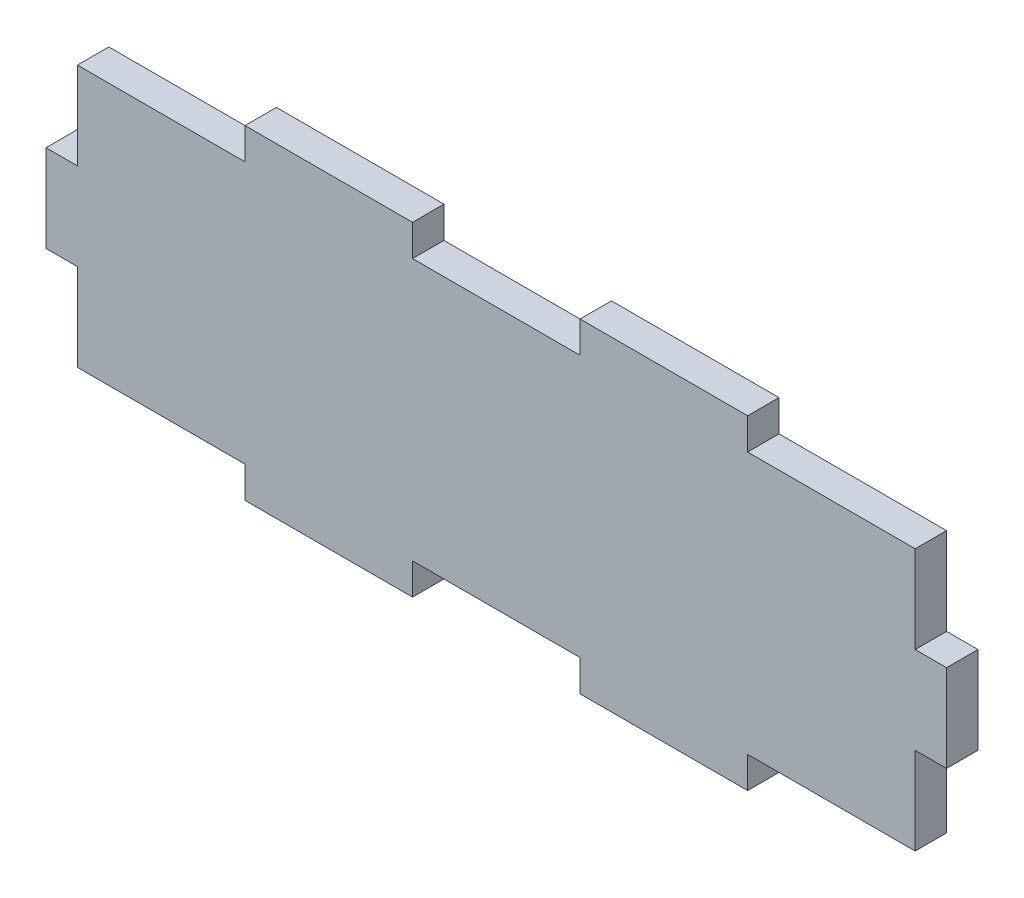
SolidWorks part; units mm, degrees
ref_plane "Front Plane" through (0, 0, 0) normal (0, 0, 1) x (1, 0, 0)
ref_plane "Top Plane" through (0, 0, 0) normal (0, 1, 0) x (1, 0, 0)
ref_plane "Right Plane" through (0, 0, 0) normal (1, 0, 0) x (0, 0, -1)
sketch "Front and Back" plane through (0, 0, 0) normal (0, 0, 1) x (1, 0, 0)
  line L0 (32, 25) -> (48, 25)
  line L1 (0, 0) -> (16, 0)
  line L2 (0, 0) -> (0, 8.3333)
  line L3 (0, 25) -> (16, 25)
  line L4 (80, 0) -> (80, 8.3333)
  line L5 (64, 25) -> (80, 25)
  line L6 (16, 25) -> (16, 28)
  line L7 (16, 28) -> (32, 28)
  line L8 (32, 25) -> (32, 28)
  line L10 (48, 25) -> (48, 28)
  line L11 (48, 28) -> (64, 28)
  line L12 (64, 25) -> (64, 28)
  line L13 (0, 16.6667) -> (-3, 16.6667)
  line L14 (80, 16.6667) -> (83, 16.6667)
  line L15 (0, 8.3333) -> (-3, 8.3333)
  line L16 (-3, 16.6667) -> (-3, 8.3333)
  line L17 (83, 16.6667) -> (83, 8.3333)
  line L18 (64, 0) -> (64, -3)
  line L19 (48, -3) -> (64, -3)
  line L20 (48, 0) -> (48, -3)
  line L21 (32, 0) -> (32, -3)
  line L22 (16, -3) -> (32, -3)
  line L23 (16, 0) -> (16, -3)
  line L24 (32, 0) -> (48, 0)
  line L25 (64, 0) -> (80, 0)
  line L26 (0, 16.6667) -> (0, 25)
  line L27 (80, 8.3333) -> (83, 8.3333)
  line L28 (80, 16.6667) -> (80, 25)
  spline B0 degree 3 poles (57.8348, 17.6005) (57.9312, 17.4182) (58.0277, 17.2901) (58.0702, 17.1461) (58.2344, 16.5888) (58.6089, 16.4324) (59.1419, 16.5492) knots 92 92 92 92 93 93 93 94 94 94 94
  spline B1 degree 3 poles (57.4613, 16.8832) (57.5503, 17.117) (57.6917, 17.3309) (57.8348, 17.6005) knots 91 91 91 91 92 92 92 92
  spline B2 degree 3 poles (56.5764, 16.555) (56.7063, 16.5483) (56.793, 16.5524) (56.8765, 16.5381) (57.1713, 16.4878) (57.352, 16.5961) (57.4613, 16.8832) knots 89 89 89 89 90 90 90 91 91 91 91
  spline B3 degree 3 poles (57.3798, 17.8947) (57.1101, 17.4634) (56.8552, 17.0227) (56.5764, 16.555) knots 88 88 88 88 89 89 89 89
  spline B4 degree 3 poles (56.6608, 19.5194) (56.9224, 19.0634) (57.1445, 18.6586) (57.3858, 18.2656) (57.4713, 18.1263) (57.4638, 18.029) (57.3798, 17.8947) knots 86 86 86 86 87 87 87 88 88 88 88
  spline B5 degree 3 poles (57.884, 18.5708) (57.7333, 18.8578) (57.6108, 19.1022) (57.4765, 19.34) (57.4373, 19.4095) (57.3695, 19.5041) (57.3062, 19.5113) (57.1087, 19.5335) (56.9071, 19.5194) (56.6608, 19.5194) knots 83 83 83 83 84 84 84 85 85 85 86 86 86 86
  spline B6 degree 3 poles (59.0504, 19.5) (58.4248, 19.5564) (58.4258, 19.5558) (58.1754, 19.0887) (58.0888, 18.927) (57.9956, 18.7687) (57.884, 18.5708) knots 81 81 81 81 82 82 82 83 83 83 83
  spline B7 degree 3 poles (58.385, 18.4147) (58.6194, 18.7587) (58.8223, 19.1241) (59.0504, 19.5) knots 80 80 80 80 81 81 81 81
  spline B8 degree 3 poles (59.1419, 16.6085) (58.8905, 17.0178) (58.6504, 17.4347) (58.3833, 17.8335) (58.243, 18.043) (58.2424, 18.2055) (58.385, 18.4147) knots 78 78 78 78 79 79 79 80 80 80 80
  spline B9 degree 3 poles (47.9997, 16.563) (47.9997, 18.0161) (47.9997, 19.4459) (47.9997, 20.8757) knots 75 75 75 75 76 76 76 76
  spline B10 degree 3 poles (47.3183, 16.563) (47.5638, 16.563) (47.7741, 16.563) (47.9997, 16.563) knots 74 74 74 74 75 75 75 75
  spline B11 degree 3 poles (47.2885, 20.8757) (47.2984, 20.7588) (47.3167, 20.642) (47.317, 20.5251) (47.3191, 19.3213) (47.3183, 18.1174) (47.3183, 16.9135) (47.3183, 16.7974) (47.3183, 16.6812) (47.3183, 16.563) knots 71 71 71 71 72 72 72 73 73 73 74 74 74 74
  spline B12 degree 3 poles (44.1082, 18.0444) (44.0494, 17.2271) (44.502, 16.5833) (45.2148, 16.5072) (45.5509, 16.4714) (45.8997, 16.5335) (46.2406, 16.5713) (46.4646, 16.5961) (46.5584, 16.7205) (46.5547, 16.973) (46.5383, 18.0878) (46.5463, 19.2029) (46.5489, 20.3179) (46.5494, 20.5039) (46.5674, 20.6898) (46.5773, 20.8757) knots 65 65 65 65 66 66 66 67 67 67 68 68 68 69 69 69 70 70 70 70
  spline B13 degree 3 poles (45.8661, 19.5113) (45.7337, 19.5283) (45.6367, 19.5434) (45.5391, 19.553) (44.9876, 19.6068) (44.4823, 19.331) (44.2765, 18.8185) (44.1792, 18.5764) (44.1271, 18.3059) (44.1082, 18.0444) knots 62 62 62 62 63 63 63 64 64 64 65 65 65 65
  spline B14 degree 3 poles (45.8661, 20.8757) (45.8661, 20.4254) (45.8661, 19.9751) (45.8661, 19.5113) knots 61 61 61 61 62 62 62 62
  spline B15 degree 3 poles (41.0823, 18.208) (40.987, 17.3397) (41.3675, 16.6466) (42.0835, 16.5363) (42.4791, 16.4754) (42.9009, 16.5616) (43.3069, 16.6134) (43.3828, 16.6231) (43.4958, 16.7841) (43.4964, 16.8759) (43.5057, 18.2091) (43.4986, 19.5424) (43.4955, 20.8757) knots 56 56 56 56 57 57 57 58 58 58 59 59 59 60 60 60 60
  spline B16 degree 3 poles (42.8435, 19.528) (41.697, 19.5891) (41.1909, 19.1969) (41.0823, 18.208) knots 55 55 55 55 56 56 56 56
  spline B17 degree 3 poles (42.8435, 20.8757) (42.8435, 20.427) (42.8435, 19.9784) (42.8435, 19.528) knots 54 54 54 54 55 55 55 55
  spline B18 degree 3 poles (20.5, 16.1343) (20.5192, 16.0502) (20.5504, 15.9668) (20.5559, 15.8818) (20.6364, 14.6346) (20.8645, 13.4153) (21.2825, 12.2375) (22.292, 9.3924) (24.0742, 7.2073) (26.7926, 5.8266) (27.0232, 5.7094) (27.2156, 5.7003) (27.4571, 5.817) (28.6739, 6.4048) (29.7303, 7.2047) (30.6365, 8.1996) (32.7117, 10.478) (33.6328, 13.2181) (33.7637, 16.2468) (33.8186, 17.518) (33.7652, 18.7937) (33.7702, 20.0673) (33.7711, 20.2886) (33.706, 20.3774) (33.4718, 20.3935) (31.7986, 20.5086) (30.1261, 20.6351) (28.4538, 20.7636) (28.1327, 20.7883) (27.8135, 20.8377) (27.4935, 20.8757) knots 43 43 43 43 44 44 44 45 45 45 46 46 46 47 47 47 48 48 48 49 49 49 50 50 50 51 51 51 52 52 52 53 53 53 53
  spline B19 degree 3 poles (35.4945, 9.4705) (35.4945, 8.1845) (35.4945, 6.9143) (35.4945, 5.6441) knots 40 40 40 40 41 41 41 41
  spline B20 degree 3 poles (35.9875, 9.4705) (35.8067, 9.4705) (35.6626, 9.4705) (35.4945, 9.4705) knots 39 39 39 39 40 40 40 40
  spline B21 degree 3 poles (35.9875, 6.042) (35.9875, 7.2088) (35.9875, 8.3383) (35.9875, 9.4705) knots 38 38 38 38 39 39 39 39
  spline B22 degree 3 poles (37.1551, 6.042) (36.7414, 6.042) (36.3818, 6.042) (35.9875, 6.042) knots 37 37 37 37 38 38 38 38
  spline B23 degree 3 poles (37.0947, 5.6441) (37.1126, 5.7621) (37.1305, 5.88) (37.1551, 6.042) knots 36 36 36 36 37 37 37 37
  spline B24 degree 3 poles (39.0505, 5.6441) (39.3828, 5.7886) (39.6262, 6.0225) (39.7383, 6.3703) (39.9127, 6.9113) (39.9172, 7.4571) (39.7273, 7.9952) (39.5642, 8.4572) (39.2016, 8.7113) (38.7195, 8.7245) (38.2416, 8.7376) (37.8597, 8.4989) (37.6814, 8.0427) (37.6035, 7.8435) (37.5549, 7.6271) (37.5296, 7.4142) (37.4284, 6.5626) (37.7015, 5.9791) (38.3393, 5.6441) knots 29 29 29 29 30 30 30 31 31 31 32 32 32 33 33 33 34 34 34 35 35 35 35
  spline B25 degree 3 poles (42.6657, 5.6441) (42.6698, 6.4014) (42.6895, 7.159) (42.6716, 7.9158) (42.6616, 8.3371) (42.4304, 8.6235) (42.0109, 8.6588) (41.5791, 8.6951) (41.1366, 8.6277) (40.7019, 8.5785) (40.6338, 8.5708) (40.5314, 8.4195) (40.5305, 8.3336) (40.521, 7.4372) (40.529, 6.5407) (40.5321, 5.6441) knots 23 23 23 23 24 24 24 25 25 25 26 26 26 27 27 27 28 28 28 28
  spline B26 degree 3 poles (45.0887, 8.6565) (44.9747, 8.6651) (44.8963, 8.6698) (44.8182, 8.6772) (44.1055, 8.7453) (43.6173, 8.4151) (43.4207, 7.7314) (43.1603, 6.8259) (43.4191, 6.1385) (44.2067, 5.6441) knots 19 19 19 19 20 20 20 21 21 21 22 22 22 22
  spline B27 degree 3 poles (45.0887, 10.0157) (45.0887, 9.5568) (45.0887, 9.1108) (45.0887, 8.6565) knots 18 18 18 18 19 19 19 19
  spline B28 degree 3 poles (45.5993, 10.0157) (45.4119, 10.0157) (45.2678, 10.0157) (45.0887, 10.0157) knots 17 17 17 17 18 18 18 18
  spline B29 degree 3 poles (45.2142, 5.6441) (45.5685, 5.7295) (45.6142, 5.9683) (45.6078, 6.299) (45.5859, 7.4323) (45.5993, 8.5664) (45.5993, 9.7001) (45.5993, 9.8043) (45.5993, 9.9085) (45.5993, 10.0157) knots 14 14 14 14 15 15 15 16 16 16 17 17 17 17
  spline B30 degree 3 poles (47.8219, 5.6441) (47.9997, 5.8058) (48.2392, 5.9351) (48.344, 6.1351) (48.7037, 6.822) (48.7111, 7.5459) (48.3379, 8.2272) (47.9912, 8.8604) (47.0257, 8.8994) (46.5725, 8.3329) (45.9642, 7.5726) (46.2209, 6.1318) (47.0515, 5.6441) knots 9 9 9 9 10 10 10 11 11 11 12 12 12 13 13 13 13
  spline B31 degree 3 poles (51.4119, 7.9139) (51.3952, 8.3441) (51.1452, 8.6282) (50.7138, 8.6667) (50.3098, 8.7028) (49.8955, 8.6378) (49.487, 8.6026) (49.3053, 8.587) (49.2369, 8.4761) (49.2395, 8.2792) (49.2512, 7.4009) (49.2444, 6.5225) (49.2443, 5.6441) knots 4 4 4 4 5 5 5 6 6 6 7 7 7 8 8 8 8
  spline B32 degree 3 poles (51.3779, 5.6441) (51.3929, 5.6803) (51.421, 5.7164) (51.421, 5.7526) (51.4224, 6.4731) (51.44, 7.1944) (51.4119, 7.9139) knots 2 2 2 2 3 3 3 4 4 4 4
  spline B33 degree 3 poles (35.8876, 16.5571) (35.9781, 17.4703) (36.0671, 18.3681) (36.1561, 19.2659) knots 15 15 15 15 16 16 16 16
  spline B34 degree 3 poles (35.2881, 16.5571) (35.5059, 16.5571) (35.6878, 16.5571) (35.8876, 16.5571) knots 14 14 14 14 15 15 15 15
  spline B35 degree 3 poles (35.7086, 20.3302) (35.5683, 19.0714) (35.429, 17.8215) (35.2881, 16.5571) knots 13 13 13 13 14 14 14 14
  spline B36 degree 3 poles (36.434, 20.3302) (36.1843, 20.3302) (35.9597, 20.3302) (35.7086, 20.3302) knots 12 12 12 12 13 13 13 13
  spline B37 degree 3 poles (37.2059, 17.576) (36.9319, 18.5538) (36.6826, 19.4431) (36.434, 20.3302) knots 11 11 11 11 12 12 12 12
  spline B38 degree 3 poles (38.005, 20.3315) (37.745, 19.4349) (37.4867, 18.544) (37.2059, 17.576) knots 10 10 10 10 11 11 11 11
  spline B39 degree 3 poles (38.7296, 20.3315) (38.4691, 20.3315) (38.2439, 20.3315) (38.005, 20.3315) knots 9 9 9 9 10 10 10 10
  spline B40 degree 3 poles (39.152, 16.5584) (39.0097, 17.829) (38.8698, 19.0789) (38.7296, 20.3315) knots 8 8 8 8 9 9 9 9
  spline B41 degree 3 poles (38.4785, 16.5584) (38.7112, 16.5584) (38.9226, 16.5584) (39.152, 16.5584) knots 7 7 7 7 8 8 8 8
  spline B42 degree 3 poles (38.2111, 19.2617) (38.2999, 18.3643) (38.3887, 17.4669) (38.4785, 16.5584) knots 6 6 6 6 7 7 7 7
  spline B43 degree 3 poles (38.1769, 19.2665) (38.1883, 19.2649) (38.1997, 19.2633) (38.2111, 19.2617) knots 5 5 5 5 6 6 6 6
  spline B44 degree 3 poles (36.1918, 19.2712) (36.4266, 18.4501) (36.6647, 17.6298) (36.8934, 16.807) (36.9393, 16.6418) (36.9766, 16.5275) (37.1951, 16.531) (37.4073, 16.5344) (37.4256, 16.6596) (37.467, 16.8047) (37.7013, 17.626) (37.9398, 18.446) (38.1769, 19.2665) knots 1 1 1 1 2 2 2 3 3 3 4 4 4 5 5 5 5
  spline B45 degree 3 poles (36.1561, 19.2659) (36.168, 19.2677) (36.1799, 19.2694) (36.1918, 19.2712) knots 0 0 0 0 1 1 1 1
  spline B46 degree 3 poles (35.4372, 14.9908) (35.4372, 14.0193) (35.4127, 13.0641) (35.4467, 12.1109) (35.4661, 11.5675) (35.9649, 11.1718) (36.5426, 11.147) (37.2785, 11.1155) (37.7848, 11.4328) (37.9126, 12.0069) (37.9232, 12.0547) (37.9302, 12.1046) (37.9303, 12.1535) (37.9313, 13.0899) (37.931, 14.0264) (37.931, 14.9906) knots 9 9 9 9 10 10 10 11 11 11 12 12 12 13 13 13 14 14 14 14
  spline B47 degree 3 poles (36.1364, 14.9908) (35.8767, 14.9908) (35.6635, 14.9908) (35.4372, 14.9908) knots 8 8 8 8 9 9 9 9
  spline B48 degree 3 poles (37.2727, 14.9906) (37.2727, 14.8669) (37.2727, 14.7603) (37.2727, 14.6538) (37.2727, 13.8648) (37.2769, 13.0758) (37.2706, 12.2869) (37.2679, 11.9362) (37.0531, 11.7065) (36.7407, 11.6911) (36.4182, 11.6752) (36.1777, 11.9016) (36.1462, 12.2563) (36.1366, 12.3641) (36.1369, 12.473) (36.1368, 12.5814) (36.136, 13.2817) (36.1364, 13.9819) (36.1364, 14.6821) (36.1364, 14.786) (36.1364, 14.8898) (36.1364, 14.9908) knots 1 1 1 1 2 2 2 3 3 3 4 4 4 5 5 5 6 6 6 7 7 7 8 8 8 8
  spline B49 degree 3 poles (37.931, 14.9906) (37.6972, 14.9906) (37.4962, 14.9906) (37.2727, 14.9906) knots 0 0 0 0 1 1 1 1
  spline B50 degree 3 poles (40.3546, 11.2163) (40.5987, 11.2163) (40.7945, 11.2163) (41.0271, 11.2163) knots 14 14 14 14 15 15 15 15
  spline B51 degree 3 poles (39.3763, 11.2183) (39.3763, 11.3365) (39.3763, 11.4427) (39.3763, 11.5489) (39.3764, 12.1898) (39.3736, 12.8308) (39.3798, 13.4716) (39.3806, 13.5622) (39.4171, 13.7269) (39.451, 13.7306) (39.6699, 13.7546) (39.9113, 13.795) (40.1073, 13.7245) (40.2252, 13.6821) (40.3367, 13.4515) (40.3434, 13.3007) (40.3701, 12.7004) (40.3545, 12.0982) (40.3546, 11.4967) (40.3546, 11.4037) (40.3546, 11.3106) (40.3546, 11.2163) knots 7 7 7 7 8 8 8 9 9 9 10 10 10 11 11 11 12 12 12 13 13 13 14 14 14 14
  spline B52 degree 3 poles (38.6853, 11.2183) (38.9321, 11.2183) (39.1363, 11.2183) (39.3763, 11.2183) knots 6 6 6 6 7 7 7 7
  spline B53 degree 3 poles (41.0271, 11.2163) (41.0271, 11.9946) (41.0454, 12.743) (41.0194, 13.4899) (41.0062, 13.8695) (40.7324, 14.0863) (40.3799, 14.1748) (39.87, 14.3029) (39.3598, 14.2583) (38.8667, 14.0919) (38.7845, 14.0642) (38.6957, 13.9124) (38.6933, 13.8159) (38.6777, 13.195) (38.6853, 12.5737) (38.6853, 11.9525) (38.6852, 11.71) (38.6853, 11.4675) (38.6853, 11.2183) knots 0 0 0 0 1 1 1 2 2 2 3 3 3 4 4 4 5 5 5 6 6 6 6
  spline B54 degree 3 poles (57.0175, 11.4332) (57.0597, 11.2969) (57.0507, 11.1231) (57.0061, 10.9858) (56.9037, 10.6709) (56.7648, 10.368) (56.6306, 10.0349) knots 10 10 10 10 11 11 11 12 12 12 12
  spline B55 degree 3 poles (56.2255, 13.8767) (56.4914, 13.0628) (56.7643, 12.2511) (57.0175, 11.4332) knots 9 9 9 9 10 10 10 10
  spline B56 degree 3 poles (56.1407, 14.1503) (56.168, 14.0622) (56.1953, 13.969) (56.2255, 13.8767) knots 8 8 8 8 9 9 9 9
  spline B57 degree 3 poles (57.4378, 12.0124) (57.2811, 12.5972) (57.1439, 13.1075) (57.0077, 13.618) (56.8395, 14.2486) (56.8398, 14.2488) (56.1787, 14.1731) (56.1705, 14.1722) (56.163, 14.164) (56.1407, 14.1503) knots 5 5 5 5 6 6 6 7 7 7 8 8 8 8
  spline B58 degree 3 poles (57.9444, 13.8116) (57.8141, 13.2309) (57.6249, 12.6635) (57.4378, 12.0124) knots 4 4 4 4 5 5 5 5
  spline B59 degree 3 poles (58.7053, 14.1736) (58.6001, 14.18) (58.5316, 14.1778) (58.4655, 14.1892) (58.1607, 14.2414) (58.0163, 14.1318) (57.9444, 13.8116) knots 2 2 2 2 3 3 3 4 4 4 4
  spline B60 degree 3 poles (57.3556, 10.0349) (57.8035, 11.4083) (58.2507, 12.7798) (58.7053, 14.1736) knots 1 1 1 1 2 2 2 2
  spline B61 degree 3 poles (56.6306, 10.0349) (56.8917, 10.0349) (57.1149, 10.0349) (57.3556, 10.0349) knots 0 0 0 0 1 1 1 1
  spline B62 degree 3 poles (49.3332, 17.7814) (49.9037, 17.8665) (50.4773, 17.9521) (51.0496, 18.0375) knots 6 6 6 6 7 7 7 7
  spline B63 degree 3 poles (50.8363, 17.1103) (49.8275, 16.8036) (49.2382, 17.069) (49.3332, 17.7814) knots 5 5 5 5 6 6 6 6
  spline B64 degree 3 poles (50.9867, 16.7135) (50.9373, 16.8437) (50.8865, 16.9778) (50.8363, 17.1103) knots 4 4 4 4 5 5 5 5
  spline B65 degree 3 poles (51.0496, 18.0375) (51.2075, 18.7243) (50.8548, 19.3846) (50.25, 19.5393) (49.534, 19.7224) (48.903, 19.3778) (48.7109, 18.6708) (48.6448, 18.428) (48.6189, 18.1646) (48.628, 17.9126) (48.6729, 16.6625) (49.881, 16.042) (50.9867, 16.7135) knots 0 0 0 0 1 1 1 2 2 2 3 3 3 4 4 4 4
  spline B66 degree 3 poles (54.5516, 17.7787) (55.1336, 17.8652) (55.7181, 17.9521) (56.3881, 18.0517) knots 8 8 8 8 9 9 9 9
  spline B67 degree 3 poles (56.0868, 17.0915) (54.9465, 16.8729) (54.54, 17.0542) (54.5516, 17.7787) knots 7 7 7 7 8 8 8 8
  spline B68 degree 3 poles (56.2409, 16.6887) (56.1824, 16.8417) (56.134, 16.9682) (56.0868, 17.0915) knots 6 6 6 6 7 7 7 7
  spline B69 degree 3 poles (54.5531, 16.6402) (55.1103, 16.3641) (55.6749, 16.4458) (56.2409, 16.6887) knots 5 5 5 5 6 6 6 6
  spline B70 degree 3 poles (53.9295, 18.603) (53.88, 18.3848) (53.8666, 18.1536) (53.8702, 17.9288) (53.879, 17.3877) (54.0331, 16.8979) (54.5531, 16.6402) knots 3 3 3 3 4 4 4 5 5 5 5
  spline B71 degree 3 poles (56.3881, 18.0517) (56.3157, 18.3754) (56.2755, 18.677) (56.178, 18.9588) (56.0678, 19.2774) (55.8108, 19.4606) (55.482, 19.5419) (54.7395, 19.7252) (54.0984, 19.3465) (53.9295, 18.603) knots 0 0 0 0 1 1 1 2 2 2 3 3 3 3
  spline B72 degree 3 poles (46.4954, 12.4424) (47.0757, 12.529) (47.6584, 12.616) (48.2697, 12.7073) knots 7 7 7 7 8 8 8 8
  spline B73 degree 3 poles (48.0191, 11.761) (46.9357, 11.5045) (46.4293, 11.7344) (46.4954, 12.4424) knots 6 6 6 6 7 7 7 7
  spline B74 degree 3 poles (48.1571, 11.3888) (48.1111, 11.513) (48.0644, 11.6389) (48.0191, 11.761) knots 5 5 5 5 6 6 6 6
  spline B75 degree 3 poles (45.9193, 13.4182) (45.8214, 13.0297) (45.7895, 12.591) (45.8621, 12.1996) (46.0468, 11.2037) (47.3239, 10.7696) (48.1571, 11.3888) knots 3 3 3 3 4 4 4 5 5 5 5
  spline B76 degree 3 poles (48.2697, 12.7073) (48.2593, 12.8781) (48.2581, 13.0342) (48.2389, 13.1879) (48.1625, 13.7978) (47.7998, 14.1794) (47.2529, 14.2341) (46.5948, 14.2999) (46.0709, 14.0197) (45.9193, 13.4182) knots 0 0 0 0 1 1 1 2 2 2 3 3 3 3
  spline B77 degree 3 poles (43.6719, 14.1753) (43.4332, 14.1753) (43.209, 14.1753) (42.9397, 14.1753) knots 9 9 9 9 10 10 10 10
  spline B78 degree 3 poles (44.2364, 12.1252) (44.049, 12.8059) (43.8615, 13.4866) (43.6719, 14.1753) knots 8 8 8 8 9 9 9 9
  spline B79 degree 3 poles (44.296, 12.1174) (44.2761, 12.12) (44.2562, 12.1226) (44.2364, 12.1252) knots 7 7 7 7 8 8 8 8
  spline B80 degree 3 poles (44.8755, 14.1721) (44.6798, 13.4782) (44.4879, 12.7978) (44.296, 12.1174) knots 6 6 6 6 7 7 7 7
  spline B81 degree 3 poles (45.5188, 14.1721) (45.2865, 14.1721) (45.0834, 14.1721) (44.8755, 14.1721) knots 5 5 5 5 6 6 6 6
  spline B82 degree 3 poles (42.9397, 14.1753) (43.2565, 13.2002) (43.5587, 12.2646) (43.868, 11.3313) (43.8849, 11.2802) (43.9544, 11.2242) (44.0089, 11.2115) (44.4199, 11.1161) (44.5663, 11.2032) (44.6913, 11.6002) (44.715, 11.6753) (44.7427, 11.7491) (44.7667, 11.8241) (45.0157, 12.6006) (45.2643, 13.3772) (45.5188, 14.1721) knots 0 0 0 0 1 1 1 2 2 2 3 3 3 4 4 4 5 5 5 5
  spline B83 degree 3 poles (54.3273, 13.762) (54.4339, 13.7423) (54.5273, 13.725) (54.64, 13.7041) knots 13 13 13 13 14 14 14 14
  spline B84 degree 3 poles (54.3273, 14.1635) (54.3273, 14.0208) (54.3273, 13.8963) (54.3273, 13.762) knots 12 12 12 12 13 13 13 13
  spline B85 degree 3 poles (54.6083, 14.2064) (54.5171, 14.1925) (54.4243, 14.1783) (54.3273, 14.1635) knots 11 11 11 11 12 12 12 12
  spline B86 degree 3 poles (55.335, 15.0405) (55.0949, 14.9676) (54.8233, 14.9636) (54.7059, 14.8271) (54.5916, 14.6943) (54.6353, 14.4256) (54.6083, 14.2064) knots 9 9 9 9 10 10 10 11 11 11 11
  spline B87 degree 3 poles (55.335, 14.2048) (55.335, 14.4841) (55.335, 14.7373) (55.335, 15.0405) knots 8 8 8 8 9 9 9 9
  spline B88 degree 3 poles (55.8049, 14.1765) (55.6448, 14.1861) (55.5018, 14.1947) (55.335, 14.2048) knots 7 7 7 7 8 8 8 8
  spline B89 degree 3 poles (55.8049, 13.754) (55.8049, 13.9007) (55.8049, 14.0339) (55.8049, 14.1765) knots 6 6 6 6 7 7 7 7
  spline B90 degree 3 poles (55.3456, 13.7129) (55.5132, 13.7279) (55.6574, 13.7408) (55.8049, 13.754) knots 5 5 5 5 6 6 6 6
  spline B91 degree 3 poles (55.3515, 11.9031) (55.3329, 12.5024) (55.3456, 13.1027) (55.3456, 13.7129) knots 4 4 4 4 5 5 5 5
  spline B92 degree 3 poles (55.8071, 11.634) (55.5815, 11.6206) (55.3597, 11.6383) (55.3515, 11.9031) knots 3 3 3 3 4 4 4 4
  spline B93 degree 3 poles (55.8071, 11.2532) (55.8071, 11.3797) (55.8071, 11.5049) (55.8071, 11.634) knots 2 2 2 2 3 3 3 3
  spline B94 degree 3 poles (54.64, 13.7041) (54.64, 13.1146) (54.6249, 12.5326) (54.644, 11.9517) (54.6653, 11.3044) (55.2208, 10.9817) (55.8071, 11.2532) knots 0 0 0 0 1 1 1 2 2 2 2
  spline B95 degree 3 poles (51.661, 17.1049) (51.6081, 16.9791) (51.5553, 16.8534) (51.4926, 16.7044) knots 15 15 15 15 16 16 16 16
  spline B96 degree 3 poles (52.6654, 17.2668) (52.5979, 17.0336) (52.3996, 16.9526) (52.1749, 16.9788) (52.0051, 16.9985) (51.8402, 17.0593) (51.661, 17.1049) knots 13 13 13 13 14 14 14 15 15 15 15
  spline B97 degree 3 poles (53.3008, 19.3659) (52.9421, 19.5873) (52.5791, 19.6326) (52.2039, 19.5314) (51.8337, 19.4315) (51.6253, 19.1716) (51.5731, 18.7928) (51.5263, 18.4545) (51.6954, 18.1541) (52.0334, 17.9725) (52.1545, 17.9074) (52.2837, 17.8574) (52.4085, 17.7991) (52.6388, 17.6917) (52.7343, 17.5047) (52.6654, 17.2668) knots 8 8 8 8 9 9 9 10 10 10 11 11 11 12 12 12 13 13 13 13
  spline B98 degree 3 poles (53.1539, 18.9957) (53.2046, 19.1233) (53.2505, 19.2392) (53.3008, 19.3659) knots 7 7 7 7 8 8 8 8
  spline B99 degree 3 poles (52.4725, 18.3874) (52.278, 18.4987) (52.1903, 18.6663) (52.2737, 18.8847) (52.3533, 19.0928) (52.5325, 19.1477) (52.7335, 19.1153) (52.8731, 19.0927) (53.0076, 19.0385) (53.1539, 18.9957) knots 4 4 4 4 5 5 5 6 6 6 7 7 7 7
  spline B100 degree 3 poles (53.3909, 17.3165) (53.4291, 17.7254) (53.2487, 18.01) (52.8176, 18.22) (52.7026, 18.276) (52.5832, 18.3241) (52.4725, 18.3874) knots 2 2 2 2 3 3 3 4 4 4 4
  spline B101 degree 3 poles (51.4926, 16.7044) (51.8655, 16.4771) (52.2441, 16.4423) (52.6293, 16.5191) (53.0635, 16.6058) (53.3546, 16.9275) (53.3909, 17.3165) knots 0 0 0 0 1 1 1 2 2 2 2
  spline B102 degree 3 poles (50.6542, 13.494) (50.5977, 13.1051) (50.7459, 12.8218) (51.1176, 12.6241) (51.2388, 12.5597) (51.3683, 12.511) (51.4926, 12.4523) (51.7142, 12.3478) (51.7879, 12.1628) (51.731, 11.9386) (51.6702, 11.6989) (51.4753, 11.6165) (51.252, 11.6397) (51.0813, 11.6575) (50.9156, 11.7233) (50.7287, 11.7728) knots 11 11 11 11 12 12 12 13 13 13 14 14 14 15 15 15 16 16 16 16
  spline B103 degree 3 poles (52.3645, 14.0217) (52.0414, 14.2473) (51.6927, 14.2797) (51.3376, 14.2142) (50.9577, 14.1442) (50.7078, 13.8626) (50.6542, 13.494) knots 9 9 9 9 10 10 10 11 11 11 11
  spline B104 degree 3 poles (52.2225, 13.6593) (52.2695, 13.7791) (52.3155, 13.8965) (52.3645, 14.0217) knots 8 8 8 8 9 9 9 9
  spline B105 degree 3 poles (51.3447, 13.5321) (51.4224, 13.6561) (51.6116, 13.751) (51.7642, 13.7751) (51.9024, 13.797) (52.0586, 13.7053) (52.2225, 13.6593) knots 6 6 6 6 7 7 7 8 8 8 8
  spline B106 degree 3 poles (52.4497, 11.941) (52.4977, 12.3709) (52.3361, 12.656) (51.9202, 12.868) (51.7888, 12.935) (51.6484, 12.9856) (51.5224, 13.061) (51.3425, 13.1686) (51.2324, 13.3531) (51.3447, 13.5321) knots 3 3 3 3 4 4 4 5 5 5 6 6 6 6
  spline B107 degree 3 poles (50.5732, 11.3811) (50.9129, 11.1538) (51.3706, 11.0835) (51.7477, 11.1914) (52.1486, 11.3062) (52.4099, 11.5852) (52.4497, 11.941) knots 1 1 1 1 2 2 2 3 3 3 3
  spline B108 degree 3 poles (50.7287, 11.7728) (50.6779, 11.645) (50.6247, 11.5109) (50.5732, 11.3811) knots 0 0 0 0 1 1 1 1
  spline B109 degree 3 poles (50.1922, 13.7754) (50.2297, 13.9094) (50.269, 14.0501) (50.3294, 14.2665) knots 8 8 8 8 9 9 9 9
  spline B110 degree 3 poles (49.5503, 11.2313) (49.5503, 11.9164) (49.5503, 12.576) (49.5502, 13.2355) (49.5502, 13.8003) (49.5502, 13.8001) (50.1245, 13.7554) (50.1423, 13.754) (50.1612, 13.7658) (50.1922, 13.7754) knots 5 5 5 5 6 6 6 7 7 7 8 8 8 8
  spline B111 degree 3 poles (48.8791, 11.2313) (49.1217, 11.2313) (49.3298, 11.2313) (49.5503, 11.2313) knots 4 4 4 4 5 5 5 5
  spline B112 degree 3 poles (50.3294, 14.2665) (49.9407, 14.2299) (49.5992, 14.2028) (49.259, 14.1644) (48.9738, 14.1321) (48.8364, 13.993) (48.8724, 13.6776) (48.9045, 13.3956) (48.8791, 13.107) (48.8791, 12.8214) (48.8791, 12.2925) (48.8791, 11.7636) (48.8791, 11.2313) knots 0 0 0 0 1 1 1 2 2 2 3 3 3 4 4 4 4
  spline B113 degree 3 poles (39.7915, 16.5519) (40.0152, 16.5519) (40.2191, 16.5519) (40.443, 16.5519) knots 3 3 3 3 4 4 4 4
  spline B114 degree 3 poles (39.7915, 19.4983) (39.7915, 18.5042) (39.7915, 17.5341) (39.7915, 16.5519) knots 2 2 2 2 3 3 3 3
  spline B115 degree 3 poles (40.443, 19.4983) (40.2127, 19.4983) (40.0027, 19.4983) (39.7915, 19.4983) knots 1 1 1 1 2 2 2 2
  spline B116 degree 3 poles (40.443, 16.5519) (40.443, 17.5576) (40.443, 18.5276) (40.443, 19.4983) knots 0 0 0 0 1 1 1 1
  spline B117 degree 3 poles (42.4426, 11.2221) (42.4426, 12.2105) (42.4426, 13.1826) (42.4426, 14.1708) knots 3 3 3 3 4 4 4 4
  spline B118 degree 3 poles (41.7916, 11.2221) (42.0202, 11.2221) (42.2239, 11.2221) (42.4426, 11.2221) knots 2 2 2 2 3 3 3 3
  spline B119 degree 3 poles (41.7916, 14.1708) (41.7916, 13.1751) (41.7916, 12.197) (41.7916, 11.2221) knots 1 1 1 1 2 2 2 2
  spline B120 degree 3 poles (42.4426, 14.1708) (42.2166, 14.1708) (42.0062, 14.1708) (41.7916, 14.1708) knots 0 0 0 0 1 1 1 1
  spline B121 degree 3 poles (53.0632, 11.2233) (53.2901, 11.2233) (53.5016, 11.2233) (53.7305, 11.2233) knots 3 3 3 3 4 4 4 4
  spline B122 degree 3 poles (53.0632, 14.17) (53.0632, 13.1816) (53.0632, 12.2113) (53.0632, 11.2233) knots 2 2 2 2 3 3 3 3
  spline B123 degree 3 poles (53.7305, 14.17) (53.5008, 14.17) (53.2893, 14.17) (53.0632, 14.17) knots 1 1 1 1 2 2 2 2
  spline B124 degree 3 poles (53.7305, 11.2233) (53.7305, 12.2233) (53.7305, 13.1943) (53.7305, 14.17) knots 0 0 0 0 1 1 1 1
  spline B125 degree 3 poles (53.7742, 15.0344) (53.7596, 15.2624) (53.6123, 15.3511) (53.4055, 15.3663) knots 3 3 3 3 4 4 4 4
  spline B126 degree 3 poles (53.4055, 15.3663) (53.1893, 15.3527) (53.0404, 15.2584) (53.0334, 15.0323) (53.0263, 14.8003) (53.1826, 14.704) (53.3895, 14.689) (53.6118, 14.6729) (53.787, 14.8333) (53.7742, 15.0344) knots 0 0 0 0 1 1 1 2 2 2 3 3 3 3
  spline B127 degree 3 poles (41.7345, 15.0244) (41.7492, 14.8022) (41.8963, 14.704) (42.1072, 14.6872) knots 3 3 3 3 4 4 4 4
  spline B128 degree 3 poles (42.4844, 15.0159) (42.4823, 15.2425) (42.3448, 15.3487) (42.1305, 15.3621) (41.9094, 15.376) (41.7215, 15.2217) (41.7345, 15.0244) knots 1 1 1 1 2 2 2 3 3 3 3
  spline B129 degree 3 poles (42.1072, 14.6872) (42.3134, 14.6846) (42.4862, 14.8277) (42.4844, 15.0159) knots 0 0 0 0 1 1 1 1
  spline B130 degree 3 poles (39.7548, 20.3582) (39.7561, 20.1176) (39.9161, 20.042) (40.1076, 20.0293) knots 3 3 3 3 4 4 4 4
  spline B131 degree 3 poles (40.1076, 20.0293) (40.3457, 20.0399) (40.494, 20.1447) (40.4895, 20.3714) (40.485, 20.5975) (40.3297, 20.7043) (40.1138, 20.7004) (39.8989, 20.6964) (39.7536, 20.5918) (39.7548, 20.3582) knots 0 0 0 0 1 1 1 2 2 2 3 3 3 3
  spline B132 degree 3 poles (26.6637, 20.8757) (26.9403, 20.8757) (27.2169, 20.8757) (27.4935, 20.8757) knots 14 14 14 14 15 15 15 15
  spline B133 degree 3 poles (20.5825, 20.386) (22.2319, 20.5088) (23.8643, 20.628) (25.4963, 20.7535) (25.8863, 20.7835) (26.2746, 20.8344) (26.6637, 20.8757) knots 12 12 12 12 13 13 13 14 14 14 14
  spline B134 degree 3 poles (20.5, 19.7496) (20.5271, 19.9585) (20.5542, 20.1674) (20.5825, 20.386) knots 11 11 11 11 12 12 12 12
  spline B135 degree 3 poles (20.5, 16.1343) (20.5, 17.3394) (20.5, 18.5445) (20.5, 19.7496) knots 10 10 10 10 11 11 11 11
  spline B136 degree 3 poles (27.4935, 20.8757) (27.8135, 20.8377) (28.1327, 20.7883) (28.4538, 20.7636) (30.1261, 20.6351) (31.7986, 20.5086) (33.4718, 20.3935) (33.706, 20.3774) (33.7711, 20.2886) (33.7702, 20.0673) (33.7652, 18.7937) (33.8186, 17.518) (33.7637, 16.2468) (33.6328, 13.2181) (32.7117, 10.478) (30.6365, 8.1996) (29.7303, 7.2047) (28.6739, 6.4048) (27.4571, 5.817) (27.2156, 5.7003) (27.0232, 5.7094) (26.7926, 5.8266) (24.0742, 7.2073) (22.292, 9.3924) (21.2825, 12.2375) (20.8645, 13.4153) (20.6364, 14.6346) (20.5559, 15.8818) (20.5504, 15.9668) (20.5192, 16.0502) (20.5, 16.1343) knots 0 0 0 0 1 1 1 2 2 2 3 3 3 4 4 4 5 5 5 6 6 6 7 7 7 8 8 8 9 9 9 10 10 10 10
  spline B137 degree 3 poles (31.8805, 12.8676) (31.788, 13.0823) (31.7569, 13.2762) (31.6449, 13.3915) (31.3256, 13.7202) (31.0128, 14.0828) (30.6267, 14.3136) (29.5524, 14.9554) (28.3458, 15.1006) (27.1181, 15.0821) (26.1906, 15.0681) (25.3076, 14.8223) (24.3607, 14.4645) knots 24 24 24 24 25 25 25 26 26 26 27 27 27 28 28 28 28
  spline B138 degree 3 poles (24.8421, 13.8049) (25.8928, 14.0853) (27.0002, 14.1301) (28.107, 13.8044) (28.3041, 13.7464) (28.441, 13.7275) (28.5903, 13.907) (28.7272, 14.0715) (28.9325, 14.1606) (29.1486, 14.0469) (29.3743, 13.9281) (29.4405, 13.6941) (29.3599, 13.486) (29.247, 13.1947) (29.4157, 13.0681) (29.5914, 12.9241) (29.6267, 12.8951) (29.6782, 12.8701) (29.7224, 12.8699) (30.4192, 12.8666) (31.116, 12.8676) (31.8805, 12.8676) knots 17 17 17 17 18 18 18 19 19 19 20 20 20 21 21 21 22 22 22 23 23 23 24 24 24 24
  spline B139 degree 3 poles (24.44, 13.5054) (24.3794, 13.4282) (24.3082, 13.3569) (24.2612, 13.2722) (24.2175, 13.1936) (24.1583, 13.0866) (24.1818, 13.0182) (24.2049, 12.9511) (24.3391, 12.863) (24.3969, 12.8797) (24.5089, 12.912) (24.6553, 12.9914) (24.691, 13.0872) (24.7701, 13.2999) (24.7896, 13.5347) (24.8421, 13.8049) knots 12 12 12 12 13 13 13 14 14 14 15 15 15 16 16 16 17 17 17 17
  spline B140 degree 3 poles (24.3774, 13.5848) (24.3982, 13.5584) (24.4191, 13.5319) (24.44, 13.5054) knots 11 11 11 11 12 12 12 12
  spline B141 degree 3 poles (24.3607, 14.4645) (24.4269, 14.6231) (24.4799, 14.7149) (24.5025, 14.8136) (24.5291, 14.9295) (24.5837, 15.0974) (24.5297, 15.1613) (24.4101, 15.303) (24.2351, 15.2343) (24.1624, 15.0915) (24.0813, 14.9319) (24.0305, 14.7436) (24.0206, 14.5647) (24.0105, 14.3817) (23.9796, 14.2627) (23.7755, 14.2438) (23.7203, 14.2387) (23.6665, 14.2076) (23.6142, 14.1839) (23.287, 14.0354) (22.9646, 13.8752) (22.6322, 13.7397) (22.3887, 13.6404) (22.4081, 13.4538) (22.4625, 13.2737) (22.5178, 13.0902) (22.6565, 12.9528) (22.8662, 13.032) (23.1732, 13.1479) (23.4643, 13.3057) (23.7707, 13.4234) (23.9649, 13.4981) (24.1746, 13.5324) (24.3774, 13.5848) knots 0 0 0 0 1 1 1 2 2 2 3 3 3 4 4 4 5 5 5 6 6 6 7 7 7 8 8 8 9 9 9 10 10 10 11 11 11 11
  spline B142 degree 3 poles (24.9161, 10.8137) (24.8959, 10.7667) (24.8902, 10.7477) (24.8803, 10.7313) (24.8246, 10.6399) (24.7548, 10.5536) (24.7215, 10.4548) (24.7136, 10.4317) (24.849, 10.3171) (24.8825, 10.331) (24.9921, 10.3766) (25.1276, 10.4413) (25.1747, 10.5372) (25.2449, 10.6802) (25.2484, 10.8561) (25.2856, 11.045) knots 20 20 20 20 21 21 21 22 22 22 23 23 23 24 24 24 25 25 25 25
  spline B143 degree 3 poles (25.019, 12.2349) (24.916, 12.2116) (24.7662, 12.2219) (24.7203, 12.1577) (24.6406, 12.0466) (24.5965, 11.8907) (24.5903, 11.7513) (24.5828, 11.5836) (24.5513, 11.4918) (24.3738, 11.4251) (24.03, 11.296) (23.6974, 11.1338) (23.3702, 10.966) (23.1963, 10.8768) (23.1807, 10.6925) (23.2929, 10.5615) (23.3691, 10.4725) (23.55, 10.3866) (23.6467, 10.4172) (24.0176, 10.5346) (24.3722, 10.7028) (24.7364, 10.8429) (24.7835, 10.861) (24.8512, 10.8256) (24.9161, 10.8137) knots 12 12 12 12 13 13 13 14 14 14 15 15 15 16 16 16 17 17 17 18 18 18 19 19 19 20 20 20 20
  spline B144 degree 3 poles (24.8908, 11.661) (24.9568, 11.7908) (25.0115, 11.8578) (25.0235, 11.9318) (25.0394, 12.03) (25.0221, 12.1336) (25.019, 12.2349) knots 10 10 10 10 11 11 11 12 12 12 12
  spline B145 degree 3 poles (31.0119, 10.3293) (30.8463, 10.6028) (30.7624, 10.8362) (30.601, 10.9866) (30.3378, 11.2321) (30.0493, 11.4777) (29.727, 11.6276) (28.6409, 12.1327) (27.4928, 12.2475) (26.3185, 12.0215) (25.8614, 11.9335) (25.4141, 11.7949) (24.8908, 11.661) knots 6 6 6 6 7 7 7 8 8 8 9 9 9 10 10 10 10
  spline B146 degree 3 poles (25.2856, 11.045) (26.0871, 11.2581) (26.9108, 11.3488) (27.7436, 11.1186) (27.9052, 11.0739) (28.0116, 11.0819) (28.1295, 11.217) (28.2742, 11.3828) (28.5017, 11.4879) (28.678, 11.3354) (28.8001, 11.2297) (28.857, 11.0033) (28.8679, 10.8262) (28.8813, 10.6088) (28.9969, 10.3447) (29.2127, 10.3365) (29.7784, 10.3151) (30.3455, 10.3293) (31.0119, 10.3293) knots 0 0 0 0 1 1 1 2 2 2 3 3 3 4 4 4 5 5 5 6 6 6 6
  spline B147 degree 3 poles (25.0345, 18.4941) (25.289, 18.4614) (25.3523, 18.2585) (25.3917, 18.0349) (25.4379, 17.7728) (25.4983, 17.5128) (25.5325, 17.2492) (25.5666, 16.986) (25.6959, 16.8079) (25.9425, 16.7213) (26.7337, 16.4435) (27.5276, 16.4442) (28.3186, 16.7196) (28.5499, 16.8002) (28.6863, 16.9628) (28.7181, 17.2198) (28.752, 17.4932) (28.8157, 17.7629) (28.8621, 18.0349) (28.9006, 18.2605) (28.9684, 18.4595) (29.2346, 18.4933) knots 20 20 20 20 21 21 21 22 22 22 23 23 23 24 24 24 25 25 25 26 26 26 27 27 27 27
  spline B148 degree 3 poles (25.9284, 18.0621) (25.8395, 18.2432) (25.6431, 18.4554) (25.6839, 18.6012) (25.7566, 18.8612) (25.5862, 18.9655) (25.4814, 19.094) (25.4213, 19.1677) (25.2141, 19.1982) (25.1256, 19.1506) (25.0371, 19.1029) (24.9897, 18.9377) (24.9698, 18.8166) (24.9542, 18.721) (25.0077, 18.614) (25.0345, 18.4941) knots 15 15 15 15 16 16 16 17 17 17 18 18 18 19 19 19 20 20 20 20
  spline B149 degree 3 poles (26.7434, 19.1424) (26.9042, 18.9515) (26.9471, 18.4083) (26.8088, 18.2319) (26.7828, 18.1988) (26.7276, 18.1789) (26.6828, 18.1718) (26.4426, 18.1335) (26.2014, 18.1011) (25.9284, 18.0621) knots 12 12 12 12 13 13 13 14 14 14 15 15 15 15
  spline B150 degree 3 poles (28.2959, 18.0527) (28.1109, 18.0876) (27.9392, 18.1292) (27.765, 18.1503) (27.5794, 18.1727) (27.3751, 18.1445) (27.3788, 18.4311) (27.3812, 18.6145) (27.2817, 18.873) (27.3688, 18.9663) (27.554, 19.1647) (27.4506, 19.3394) (27.402, 19.5005) (27.373, 19.5968) (27.2017, 19.7129) (27.1008, 19.7071) (27.0006, 19.7013) (26.8863, 19.5683) (26.8196, 19.4645) (26.7634, 19.377) (26.7665, 19.2513) (26.7434, 19.1424) knots 5 5 5 5 6 6 6 7 7 7 8 8 8 9 9 9 10 10 10 11 11 11 12 12 12 12
  spline B151 degree 3 poles (29.2346, 18.4933) (29.2429, 18.5804) (29.2607, 18.6549) (29.2548, 18.7275) (29.2438, 18.8628) (29.2537, 19.019) (29.187, 19.1231) (29.1478, 19.1843) (28.9409, 19.2137) (28.8748, 19.1663) (28.7428, 19.0715) (28.5421, 18.8778) (28.5704, 18.7887) (28.6803, 18.4424) (28.4101, 18.2905) (28.2959, 18.0527) knots 0 0 0 0 1 1 1 2 2 2 3 3 3 4 4 4 5 5 5 5
  spline B152 degree 3 poles (25.7694, 8.7126) (26.3209, 8.8594) (26.8818, 8.9039) (27.4564, 8.8069) (27.5625, 8.7889) (27.6823, 8.8513) (27.7956, 8.8773) (27.9398, 8.9103) (28.1281, 9.0149) (28.2167, 8.9595) (28.3268, 8.8905) (28.4174, 8.6836) (28.4041, 8.5473) (28.3798, 8.2991) (28.5236, 8.1964) (28.6907, 8.1847) (29.1106, 8.1554) (29.5338, 8.175) (29.9771, 8.175) knots 17 17 17 17 18 18 18 19 19 19 20 20 20 21 21 21 22 22 22 23 23 23 23
  spline B153 degree 3 poles (25.4067, 8.5329) (25.3663, 8.3962) (25.3233, 8.2858) (25.309, 8.1718) (25.3062, 8.1497) (25.4475, 8.0744) (25.4666, 8.0903) (25.566, 8.1734) (25.6693, 8.2666) (25.7282, 8.3789) (25.774, 8.4664) (25.7566, 8.587) (25.7694, 8.7126) knots 13 13 13 13 14 14 14 15 15 15 16 16 16 17 17 17 17
  spline B154 degree 3 poles (25.5531, 9.7118) (25.4652, 9.6945) (25.3369, 9.7067) (25.2984, 9.6536) (25.2287, 9.5575) (25.1843, 9.4233) (25.1811, 9.3035) (25.1767, 9.1447) (25.1504, 9.0681) (24.9742, 9.0146) (24.7204, 8.9377) (24.4762, 8.8116) (24.2505, 8.6703) (24.1781, 8.625) (24.1252, 8.4428) (24.1589, 8.3641) (24.1914, 8.2878) (24.3647, 8.204) (24.445, 8.2279) (24.7372, 8.3153) (25.0152, 8.4494) (25.3018, 8.5572) (25.3395, 8.5714) (25.396, 8.5357) (25.4067, 8.5329) knots 5 5 5 5 6 6 6 7 7 7 8 8 8 9 9 9 10 10 10 11 11 11 12 12 12 13 13 13 13
  spline B155 degree 3 poles (25.4434, 9.2392) (25.4996, 9.3336) (25.5545, 9.3895) (25.5653, 9.4529) (25.5794, 9.5361) (25.5588, 9.6252) (25.5531, 9.7118) knots 3 3 3 3 4 4 4 5 5 5 5
  spline B156 degree 3 poles (29.9771, 8.175) (29.8908, 8.6029) (29.6978, 8.861) (29.2726, 9.0928) (28.4928, 9.518) (27.6461, 9.6207) (26.7796, 9.5243) (26.3482, 9.4764) (25.9261, 9.3452) (25.4434, 9.2392) knots 0 0 0 0 1 1 1 2 2 2 3 3 3 3
  spline B157 degree 3 poles (45.8661, 20.8757) (46.1032, 20.8757) (46.3403, 20.8757) (46.5773, 20.8757) knots 9 9 9 9 10 10 10 10
  spline B158 degree 3 poles (45.8661, 19.5113) (45.8661, 19.9751) (45.8661, 20.4254) (45.8661, 20.8757) knots 8 8 8 8 9 9 9 9
  spline B159 degree 3 poles (44.1082, 18.0444) (44.1271, 18.3059) (44.1792, 18.5764) (44.2765, 18.8185) (44.4823, 19.331) (44.9876, 19.6068) (45.5391, 19.553) (45.6367, 19.5434) (45.7337, 19.5283) (45.8661, 19.5113) knots 5 5 5 5 6 6 6 7 7 7 8 8 8 8
  spline B160 degree 3 poles (46.5773, 20.8757) (46.5674, 20.6898) (46.5494, 20.5039) (46.5489, 20.3179) (46.5463, 19.2029) (46.5383, 18.0878) (46.5547, 16.973) (46.5584, 16.7205) (46.4646, 16.5961) (46.2406, 16.5713) (45.8997, 16.5335) (45.5509, 16.4714) (45.2148, 16.5072) (44.502, 16.5833) (44.0494, 17.2271) (44.1082, 18.0444) knots 0 0 0 0 1 1 1 2 2 2 3 3 3 4 4 4 5 5 5 5
  spline B161 degree 3 poles (44.8549, 17.5589) (44.9415, 17.0124) (45.2953, 16.8293) (45.8664, 16.9928) knots 4 4 4 4 5 5 5 5
  spline B162 degree 3 poles (45.8664, 16.9928) (45.8664, 17.5752) (45.8664, 18.1468) (45.8664, 18.7184) (45.8663, 19.159) (45.6388, 19.3073) (45.249, 19.076) (45.0874, 18.9801) (44.918, 18.7839) (44.8853, 18.6084) (44.8216, 18.2673) (44.8009, 17.9004) (44.8549, 17.5589) knots 0 0 0 0 1 1 1 2 2 2 3 3 3 4 4 4 4
  spline B163 degree 3 poles (42.8435, 20.8757) (43.0608, 20.8757) (43.2782, 20.8757) (43.4955, 20.8757) knots 6 6 6 6 7 7 7 7
  spline B164 degree 3 poles (42.8435, 19.528) (42.8435, 19.9784) (42.8435, 20.427) (42.8435, 20.8757) knots 5 5 5 5 6 6 6 6
  spline B165 degree 3 poles (41.0823, 18.208) (41.1909, 19.1969) (41.697, 19.5891) (42.8435, 19.528) knots 4 4 4 4 5 5 5 5
  spline B166 degree 3 poles (43.4955, 20.8757) (43.4986, 19.5424) (43.5057, 18.2091) (43.4964, 16.8759) (43.4958, 16.7841) (43.3828, 16.6231) (43.3069, 16.6134) (42.9009, 16.5616) (42.4791, 16.4754) (42.0835, 16.5363) (41.3675, 16.6466) (40.987, 17.3397) (41.0823, 18.208) knots 0 0 0 0 1 1 1 2 2 2 3 3 3 4 4 4 4
  spline B167 degree 3 poles (41.8651, 18.6513) (41.7948, 18.283) (41.7752, 17.8856) (41.8338, 17.5169) (41.9166, 16.9959) (42.2962, 16.8204) (42.8322, 16.999) knots 3 3 3 3 4 4 4 5 5 5 5
  spline B168 degree 3 poles (42.8322, 16.999) (42.8322, 17.6578) (42.8361, 18.3267) (42.8247, 18.9953) (42.8238, 19.0485) (42.7233, 19.1325) (42.6572, 19.1466) (42.3052, 19.2218) (41.9365, 19.0257) (41.8651, 18.6513) knots 0 0 0 0 1 1 1 2 2 2 3 3 3 3
  spline B169 degree 3 poles (45.2142, 5.6441) (44.8784, 5.6441) (44.5425, 5.6441) (44.2067, 5.6441) knots 8 8 8 8 9 9 9 9
  spline B170 degree 3 poles (45.5993, 10.0157) (45.5993, 9.9085) (45.5993, 9.8043) (45.5993, 9.7001) (45.5993, 8.5664) (45.5859, 7.4323) (45.6078, 6.299) (45.6142, 5.9683) (45.5685, 5.7295) (45.2142, 5.6441) knots 5 5 5 5 6 6 6 7 7 7 8 8 8 8
  spline B171 degree 3 poles (45.0887, 10.0157) (45.2678, 10.0157) (45.4119, 10.0157) (45.5993, 10.0157) knots 4 4 4 4 5 5 5 5
  spline B172 degree 3 poles (45.0887, 8.6565) (45.0887, 9.1108) (45.0887, 9.5568) (45.0887, 10.0157) knots 3 3 3 3 4 4 4 4
  spline B173 degree 3 poles (44.2067, 5.6441) (43.4191, 6.1385) (43.1603, 6.8259) (43.4207, 7.7314) (43.6173, 8.4151) (44.1055, 8.7453) (44.8182, 8.6772) (44.8963, 8.6698) (44.9747, 8.6651) (45.0887, 8.6565) knots 0 0 0 0 1 1 1 2 2 2 3 3 3 3
  spline B174 degree 3 poles (45.0956, 6.0604) (45.0956, 6.7622) (45.0959, 7.4713) (45.095, 8.1804) (45.0949, 8.2283) (45.0864, 8.2761) (45.0805, 8.3377) knots 3 3 3 3 4 4 4 5 5 5 5
  spline B175 degree 3 poles (45.0805, 8.3377) (44.4569, 8.465) (44.0384, 8.2908) (43.9383, 7.7771) (43.8599, 7.3746) (43.8597, 6.9302) (43.9436, 6.5293) (44.0554, 5.9953) (44.5729, 5.8138) (45.0956, 6.0604) knots 0 0 0 0 1 1 1 2 2 2 3 3 3 3
  spline B176 degree 3 poles (59.1419, 16.6085) (59.1419, 16.5887) (59.1419, 16.569) (59.1419, 16.5492) knots 16 16 16 16 17 17 17 17
  spline B177 degree 3 poles (58.385, 18.4147) (58.2424, 18.2055) (58.243, 18.043) (58.3833, 17.8335) (58.6504, 17.4347) (58.8905, 17.0178) (59.1419, 16.6085) knots 14 14 14 14 15 15 15 16 16 16 16
  spline B178 degree 3 poles (59.0504, 19.5) (58.8223, 19.1241) (58.6194, 18.7587) (58.385, 18.4147) knots 13 13 13 13 14 14 14 14
  spline B179 degree 3 poles (57.884, 18.5708) (57.9956, 18.7687) (58.0888, 18.927) (58.1754, 19.0887) (58.4258, 19.5558) (58.4248, 19.5564) (59.0504, 19.5) knots 11 11 11 11 12 12 12 13 13 13 13
  spline B180 degree 3 poles (56.6608, 19.5194) (56.9071, 19.5194) (57.1087, 19.5335) (57.3062, 19.5113) (57.3695, 19.5041) (57.4373, 19.4095) (57.4765, 19.34) (57.6108, 19.1022) (57.7333, 18.8578) (57.884, 18.5708) knots 8 8 8 8 9 9 9 10 10 10 11 11 11 11
  spline B181 degree 3 poles (57.3798, 17.8947) (57.4638, 18.029) (57.4713, 18.1263) (57.3858, 18.2656) (57.1445, 18.6586) (56.9224, 19.0634) (56.6608, 19.5194) knots 6 6 6 6 7 7 7 8 8 8 8
  spline B182 degree 3 poles (56.5764, 16.555) (56.8552, 17.0227) (57.1101, 17.4634) (57.3798, 17.8947) knots 5 5 5 5 6 6 6 6
  spline B183 degree 3 poles (57.4613, 16.8832) (57.352, 16.5961) (57.1713, 16.4878) (56.8765, 16.5381) (56.793, 16.5524) (56.7063, 16.5483) (56.5764, 16.555) knots 3 3 3 3 4 4 4 5 5 5 5
  spline B184 degree 3 poles (57.8348, 17.6005) (57.6917, 17.3309) (57.5503, 17.117) (57.4613, 16.8832) knots 2 2 2 2 3 3 3 3
  spline B185 degree 3 poles (59.1419, 16.5492) (58.6089, 16.4324) (58.2344, 16.5888) (58.0702, 17.1461) (58.0277, 17.2901) (57.9312, 17.4182) (57.8348, 17.6005) knots 0 0 0 0 1 1 1 2 2 2 2
  spline B186 degree 3 poles (49.7185, 5.6441) (49.5604, 5.6441) (49.4024, 5.6441) (49.2443, 5.6441) knots 12 12 12 12 13 13 13 13
  spline B187 degree 3 poles (50.9108, 7.8215) (50.9044, 8.2422) (50.6974, 8.3941) (50.1893, 8.3802) (49.7684, 8.3687) (49.7516, 8.3448) (49.7472, 7.8576) (49.7405, 7.1197) (49.7283, 6.382) (49.7185, 5.6441) knots 9 9 9 9 10 10 10 11 11 11 12 12 12 12
  spline B188 degree 3 poles (50.9631, 5.6441) (50.9467, 5.7492) (50.9168, 5.8541) (50.916, 5.9592) (50.9113, 6.58) (50.9202, 7.2009) (50.9108, 7.8215) knots 7 7 7 7 8 8 8 9 9 9 9
  spline B189 degree 3 poles (51.3779, 5.6441) (51.2396, 5.6441) (51.1014, 5.6441) (50.9631, 5.6441) knots 6 6 6 6 7 7 7 7
  spline B190 degree 3 poles (51.4119, 7.9139) (51.44, 7.1944) (51.4224, 6.4731) (51.421, 5.7526) (51.421, 5.7164) (51.3929, 5.6803) (51.3779, 5.6441) knots 4 4 4 4 5 5 5 6 6 6 6
  spline B191 degree 3 poles (49.2443, 5.6441) (49.2444, 6.5225) (49.2512, 7.4009) (49.2395, 8.2792) (49.2369, 8.4761) (49.3053, 8.587) (49.487, 8.6026) (49.8955, 8.6378) (50.3098, 8.7028) (50.7138, 8.6667) (51.1452, 8.6282) (51.3952, 8.3441) (51.4119, 7.9139) knots 0 0 0 0 1 1 1 2 2 2 3 3 3 4 4 4 4
  spline B192 degree 3 poles (47.8219, 5.6441) (47.5651, 5.6441) (47.3083, 5.6441) (47.0515, 5.6441) knots 4 4 4 4 5 5 5 5
  spline B193 degree 3 poles (47.0515, 5.6441) (46.2209, 6.1318) (45.9642, 7.5726) (46.5725, 8.3329) (47.0257, 8.8994) (47.9912, 8.8604) (48.3379, 8.2272) (48.7111, 7.5459) (48.7037, 6.822) (48.344, 6.1351) (48.2392, 5.9351) (47.9997, 5.8058) (47.8219, 5.6441) knots 0 0 0 0 1 1 1 2 2 2 3 3 3 4 4 4 4
  spline B194 degree 3 poles (47.9647, 7.996) (47.8837, 8.2417) (47.7004, 8.3887) (47.4333, 8.3927) (47.1528, 8.3969) (46.9561, 8.2487) (46.8797, 7.9886) (46.8029, 7.7272) (46.7694, 7.4532) (46.7148, 7.1742) knots 4 4 4 4 5 5 5 6 6 6 7 7 7 7
  spline B195 degree 3 poles (46.7148, 7.1742) (46.7692, 6.9012) (46.8035, 6.6274) (46.8813, 6.3666) (46.9596, 6.1043) (47.1636, 5.9691) (47.4421, 5.9737) (47.7111, 5.9781) (47.8941, 6.1263) (47.9721, 6.3712) (48.144, 6.9107) (48.1421, 7.4576) (47.9647, 7.996) knots 0 0 0 0 1 1 1 2 2 2 3 3 3 4 4 4 4
  spline B196 degree 3 poles (41.0063, 5.6441) (40.8482, 5.6441) (40.6902, 5.6441) (40.5321, 5.6441) knots 10 10 10 10 11 11 11 11
  spline B197 degree 3 poles (42.1916, 5.6441) (42.1917, 6.2936) (42.192, 6.943) (42.1918, 7.5924) (42.1915, 8.2627) (41.9687, 8.4562) (41.3079, 8.3725) (41.101, 8.3463) (41.0062, 8.2699) (41.0099, 8.0354) (41.0224, 7.2385) (41.0095, 6.4413) (41.0063, 5.6441) knots 6 6 6 6 7 7 7 8 8 8 9 9 9 10 10 10 10
  spline B198 degree 3 poles (42.6657, 5.6441) (42.5077, 5.6441) (42.3496, 5.6441) (42.1916, 5.6441) knots 5 5 5 5 6 6 6 6
  spline B199 degree 3 poles (40.5321, 5.6441) (40.529, 6.5407) (40.521, 7.4372) (40.5305, 8.3336) (40.5314, 8.4195) (40.6338, 8.5708) (40.7019, 8.5785) (41.1366, 8.6277) (41.5791, 8.6951) (42.0109, 8.6588) (42.4304, 8.6235) (42.6616, 8.3371) (42.6716, 7.9158) (42.6895, 7.159) (42.6698, 6.4014) (42.6657, 5.6441) knots 0 0 0 0 1 1 1 2 2 2 3 3 3 4 4 4 5 5 5 5
  spline B200 degree 3 poles (39.0505, 5.6441) (38.8134, 5.6441) (38.5763, 5.6441) (38.3393, 5.6441) knots 6 6 6 6 7 7 7 7
  spline B201 degree 3 poles (38.3393, 5.6441) (37.7015, 5.9791) (37.4284, 6.5626) (37.5296, 7.4142) (37.5549, 7.6271) (37.6035, 7.8435) (37.6814, 8.0427) (37.8597, 8.4989) (38.2416, 8.7376) (38.7195, 8.7245) (39.2016, 8.7113) (39.5642, 8.4572) (39.7273, 7.9952) (39.9172, 7.4571) (39.9127, 6.9113) (39.7383, 6.3703) (39.6262, 6.0225) (39.3828, 5.7886) (39.0505, 5.6441) knots 0 0 0 0 1 1 1 2 2 2 3 3 3 4 4 4 5 5 5 6 6 6 6
  spline B202 degree 3 poles (39.2366, 7.9875) (39.1529, 8.2487) (38.9644, 8.3974) (38.6842, 8.3927) (38.4042, 8.388) (38.2144, 8.2304) (38.1422, 7.9706) (38.0718, 7.7177) (38.0439, 7.4529) (37.9926, 7.1672) knots 4 4 4 4 5 5 5 6 6 6 7 7 7 7
  spline B203 degree 3 poles (38.703, 5.9738) (38.9689, 5.9776) (39.1554, 6.1127) (39.2374, 6.3631) (39.4144, 6.9029) (39.4096, 7.4478) (39.2366, 7.9875) knots 2 2 2 2 3 3 3 4 4 4 4
  spline B204 degree 3 poles (37.9926, 7.1672) (38.045, 6.9011) (38.0792, 6.6176) (38.1601, 6.3482) (38.2353, 6.098) (38.4371, 5.97) (38.703, 5.9738) knots 0 0 0 0 1 1 1 2 2 2 2
  spline B205 degree 3 poles (41.0063, 5.6441) (41.0095, 6.4413) (41.0224, 7.2385) (41.0099, 8.0354) (41.0062, 8.2699) (41.101, 8.3463) (41.3079, 8.3725) (41.9687, 8.4562) (42.1915, 8.2627) (42.1918, 7.5924) (42.192, 6.943) (42.1917, 6.2936) (42.1916, 5.6441) knots 0 0 0 0 1 1 1 2 2 2 3 3 3 4 4 4 4
  spline B206 degree 3 poles (47.2885, 20.8757) (47.5256, 20.8757) (47.7627, 20.8757) (47.9997, 20.8757) knots 5 5 5 5 6 6 6 6
  spline B207 degree 3 poles (47.3183, 16.563) (47.3183, 16.6812) (47.3183, 16.7974) (47.3183, 16.9135) (47.3183, 18.1174) (47.3191, 19.3213) (47.317, 20.5251) (47.3167, 20.642) (47.2984, 20.7588) (47.2885, 20.8757) knots 2 2 2 2 3 3 3 4 4 4 5 5 5 5
  spline B208 degree 3 poles (47.9997, 16.563) (47.7741, 16.563) (47.5638, 16.563) (47.3183, 16.563) knots 1 1 1 1 2 2 2 2
  spline B209 degree 3 poles (47.9997, 20.8757) (47.9997, 19.4459) (47.9997, 18.0161) (47.9997, 16.563) knots 0 0 0 0 1 1 1 1
  spline B210 degree 3 poles (50.9108, 7.8215) (50.9202, 7.2009) (50.9113, 6.58) (50.916, 5.9592) (50.9168, 5.8541) (50.9467, 5.7492) (50.9631, 5.6441) knots 3 3 3 3 4 4 4 5 5 5 5
  spline B211 degree 3 poles (49.7185, 5.6441) (49.7283, 6.382) (49.7405, 7.1197) (49.7472, 7.8576) (49.7516, 8.3448) (49.7684, 8.3687) (50.1893, 8.3802) (50.6974, 8.3941) (50.9044, 8.2422) (50.9108, 7.8215) knots 0 0 0 0 1 1 1 2 2 2 3 3 3 3
  spline B212 degree 3 poles (37.0947, 5.6441) (36.5613, 5.6441) (36.0279, 5.6441) (35.4945, 5.6441) knots 5 5 5 5 6 6 6 6
  spline B213 degree 3 poles (37.1551, 6.042) (37.1305, 5.88) (37.1126, 5.7621) (37.0947, 5.6441) knots 4 4 4 4 5 5 5 5
  spline B214 degree 3 poles (35.9875, 6.042) (36.3818, 6.042) (36.7414, 6.042) (37.1551, 6.042) knots 3 3 3 3 4 4 4 4
  spline B215 degree 3 poles (35.9875, 9.4705) (35.9875, 8.3383) (35.9875, 7.2088) (35.9875, 6.042) knots 2 2 2 2 3 3 3 3
  spline B216 degree 3 poles (35.4945, 9.4705) (35.6626, 9.4705) (35.8067, 9.4705) (35.9875, 9.4705) knots 1 1 1 1 2 2 2 2
  spline B217 degree 3 poles (35.4945, 5.6441) (35.4945, 6.9143) (35.4945, 8.1845) (35.4945, 9.4705) knots 0 0 0 0 1 1 1 1
  spline B218 degree 3 poles (20.5825, 20.386) (20.5542, 20.1674) (20.5271, 19.9585) (20.5, 19.7496) knots 2 2 2 2 3 3 3 3
  spline B219 degree 3 poles (26.6637, 20.8757) (26.2746, 20.8344) (25.8863, 20.7835) (25.4963, 20.7535) (23.8643, 20.628) (22.2319, 20.5088) (20.5825, 20.386) knots 0 0 0 0 1 1 1 2 2 2 2
  spline B220 degree 3 poles (36.1918, 19.2712) (36.1799, 19.2694) (36.168, 19.2677) (36.1561, 19.2659) knots 15 15 15 15 16 16 16 16
  spline B221 degree 3 poles (38.1769, 19.2665) (37.9398, 18.446) (37.7013, 17.626) (37.467, 16.8047) (37.4256, 16.6596) (37.4073, 16.5344) (37.1951, 16.531) (36.9766, 16.5275) (36.9393, 16.6418) (36.8934, 16.807) (36.6647, 17.6298) (36.4266, 18.4501) (36.1918, 19.2712) knots 11 11 11 11 12 12 12 13 13 13 14 14 14 15 15 15 15
  spline B222 degree 3 poles (38.2111, 19.2617) (38.1997, 19.2633) (38.1883, 19.2649) (38.1769, 19.2665) knots 10 10 10 10 11 11 11 11
  spline B223 degree 3 poles (38.4785, 16.5584) (38.3887, 17.4669) (38.2999, 18.3643) (38.2111, 19.2617) knots 9 9 9 9 10 10 10 10
  spline B224 degree 3 poles (39.152, 16.5584) (38.9226, 16.5584) (38.7112, 16.5584) (38.4785, 16.5584) knots 8 8 8 8 9 9 9 9
  spline B225 degree 3 poles (38.7296, 20.3315) (38.8698, 19.0789) (39.0097, 17.829) (39.152, 16.5584) knots 7 7 7 7 8 8 8 8
  spline B226 degree 3 poles (38.005, 20.3315) (38.2439, 20.3315) (38.4691, 20.3315) (38.7296, 20.3315) knots 6 6 6 6 7 7 7 7
  spline B227 degree 3 poles (37.2059, 17.576) (37.4867, 18.544) (37.745, 19.4349) (38.005, 20.3315) knots 5 5 5 5 6 6 6 6
  spline B228 degree 3 poles (36.434, 20.3302) (36.6826, 19.4431) (36.9319, 18.5538) (37.2059, 17.576) knots 4 4 4 4 5 5 5 5
  spline B229 degree 3 poles (35.7086, 20.3302) (35.9597, 20.3302) (36.1843, 20.3302) (36.434, 20.3302) knots 3 3 3 3 4 4 4 4
  spline B230 degree 3 poles (35.2881, 16.5571) (35.429, 17.8215) (35.5683, 19.0714) (35.7086, 20.3302) knots 2 2 2 2 3 3 3 3
  spline B231 degree 3 poles (35.8876, 16.5571) (35.6878, 16.5571) (35.5059, 16.5571) (35.2881, 16.5571) knots 1 1 1 1 2 2 2 2
  spline B232 degree 3 poles (36.1561, 19.2659) (36.0671, 18.3681) (35.9781, 17.4703) (35.8876, 16.5571) knots 0 0 0 0 1 1 1 1
  spline B233 degree 3 poles (37.2727, 14.9906) (37.4962, 14.9906) (37.6972, 14.9906) (37.931, 14.9906) knots 13 13 13 13 14 14 14 14
  spline B234 degree 3 poles (36.1364, 14.9908) (36.1364, 14.8898) (36.1364, 14.786) (36.1364, 14.6821) (36.1364, 13.9819) (36.136, 13.2817) (36.1368, 12.5814) (36.1369, 12.473) (36.1366, 12.3641) (36.1462, 12.2563) (36.1777, 11.9016) (36.4182, 11.6752) (36.7407, 11.6911) (37.0531, 11.7065) (37.2679, 11.9362) (37.2706, 12.2869) (37.2769, 13.0758) (37.2727, 13.8648) (37.2727, 14.6538) (37.2727, 14.7603) (37.2727, 14.8669) (37.2727, 14.9906) knots 6 6 6 6 7 7 7 8 8 8 9 9 9 10 10 10 11 11 11 12 12 12 13 13 13 13
  spline B235 degree 3 poles (35.4372, 14.9908) (35.6635, 14.9908) (35.8767, 14.9908) (36.1364, 14.9908) knots 5 5 5 5 6 6 6 6
  spline B236 degree 3 poles (37.931, 14.9906) (37.931, 14.0264) (37.9313, 13.0899) (37.9303, 12.1535) (37.9302, 12.1046) (37.9232, 12.0547) (37.9126, 12.0069) (37.7848, 11.4328) (37.2785, 11.1155) (36.5426, 11.147) (35.9649, 11.1718) (35.4661, 11.5675) (35.4467, 12.1109) (35.4127, 13.0641) (35.4372, 14.0193) (35.4372, 14.9908) knots 0 0 0 0 1 1 1 2 2 2 3 3 3 4 4 4 5 5 5 5
  spline B237 degree 3 poles (38.6853, 11.2183) (38.6853, 11.4675) (38.6852, 11.71) (38.6853, 11.9525) (38.6853, 12.5737) (38.6777, 13.195) (38.6933, 13.8159) (38.6957, 13.9124) (38.7845, 14.0642) (38.8667, 14.0919) (39.3598, 14.2583) (39.87, 14.3029) (40.3799, 14.1748) (40.7324, 14.0863) (41.0062, 13.8695) (41.0194, 13.4899) (41.0454, 12.743) (41.0271, 11.9946) (41.0271, 11.2163) knots 9 9 9 9 10 10 10 11 11 11 12 12 12 13 13 13 14 14 14 15 15 15 15
  spline B238 degree 3 poles (39.3763, 11.2183) (39.1363, 11.2183) (38.9321, 11.2183) (38.6853, 11.2183) knots 8 8 8 8 9 9 9 9
  spline B239 degree 3 poles (40.3546, 11.2163) (40.3546, 11.3106) (40.3546, 11.4037) (40.3546, 11.4967) (40.3545, 12.0982) (40.3701, 12.7004) (40.3434, 13.3007) (40.3367, 13.4515) (40.2252, 13.6821) (40.1073, 13.7245) (39.9113, 13.795) (39.6699, 13.7546) (39.451, 13.7306) (39.4171, 13.7269) (39.3806, 13.5622) (39.3798, 13.4716) (39.3736, 12.8308) (39.3764, 12.1898) (39.3763, 11.5489) (39.3763, 11.4427) (39.3763, 11.3365) (39.3763, 11.2183) knots 1 1 1 1 2 2 2 3 3 3 4 4 4 5 5 5 6 6 6 7 7 7 8 8 8 8
  spline B240 degree 3 poles (41.0271, 11.2163) (40.7945, 11.2163) (40.5987, 11.2163) (40.3546, 11.2163) knots 0 0 0 0 1 1 1 1
  spline B241 degree 3 poles (57.3556, 10.0349) (57.1149, 10.0349) (56.8917, 10.0349) (56.6306, 10.0349) knots 11 11 11 11 12 12 12 12
  spline B242 degree 3 poles (58.7053, 14.1736) (58.2507, 12.7798) (57.8035, 11.4083) (57.3556, 10.0349) knots 10 10 10 10 11 11 11 11
  spline B243 degree 3 poles (57.9444, 13.8116) (58.0163, 14.1318) (58.1607, 14.2414) (58.4655, 14.1892) (58.5316, 14.1778) (58.6001, 14.18) (58.7053, 14.1736) knots 8 8 8 8 9 9 9 10 10 10 10
  spline B244 degree 3 poles (57.4378, 12.0124) (57.6249, 12.6635) (57.8141, 13.2309) (57.9444, 13.8116) knots 7 7 7 7 8 8 8 8
  spline B245 degree 3 poles (56.1407, 14.1503) (56.163, 14.164) (56.1705, 14.1722) (56.1787, 14.1731) (56.8398, 14.2488) (56.8395, 14.2486) (57.0077, 13.618) (57.1439, 13.1075) (57.2811, 12.5972) (57.4378, 12.0124) knots 4 4 4 4 5 5 5 6 6 6 7 7 7 7
  spline B246 degree 3 poles (56.2255, 13.8767) (56.1953, 13.969) (56.168, 14.0622) (56.1407, 14.1503) knots 3 3 3 3 4 4 4 4
  spline B247 degree 3 poles (57.0175, 11.4332) (56.7643, 12.2511) (56.4914, 13.0628) (56.2255, 13.8767) knots 2 2 2 2 3 3 3 3
  spline B248 degree 3 poles (56.6306, 10.0349) (56.7648, 10.368) (56.9037, 10.6709) (57.0061, 10.9858) (57.0507, 11.1231) (57.0597, 11.2969) (57.0175, 11.4332) knots 0 0 0 0 1 1 1 2 2 2 2
  spline B249 degree 3 poles (50.9867, 16.7135) (49.881, 16.042) (48.6729, 16.6625) (48.628, 17.9126) (48.6189, 18.1646) (48.6448, 18.428) (48.7109, 18.6708) (48.903, 19.3778) (49.534, 19.7224) (50.25, 19.5393) (50.8548, 19.3846) (51.2075, 18.7243) (51.0496, 18.0375) knots 3 3 3 3 4 4 4 5 5 5 6 6 6 7 7 7 7
  spline B250 degree 3 poles (50.8363, 17.1103) (50.8865, 16.9778) (50.9373, 16.8437) (50.9867, 16.7135) knots 2 2 2 2 3 3 3 3
  spline B251 degree 3 poles (49.3332, 17.7814) (49.2382, 17.069) (49.8275, 16.8036) (50.8363, 17.1103) knots 1 1 1 1 2 2 2 2
  spline B252 degree 3 poles (51.0496, 18.0375) (50.4773, 17.9521) (49.9037, 17.8665) (49.3332, 17.7814) knots 0 0 0 0 1 1 1 1
  spline B253 degree 3 poles (49.2494, 18.1363) (49.6642, 18.2011) (50.0409, 18.26) (50.4377, 18.322) knots 3 3 3 3 4 4 4 4
  spline B254 degree 3 poles (49.539, 19.0186) (49.2478, 18.8207) (49.2277, 18.4868) (49.2494, 18.1363) knots 2 2 2 2 3 3 3 3
  spline B255 degree 3 poles (50.4377, 18.322) (50.4396, 18.6586) (50.4278, 18.9738) (50.1096, 19.0855) (49.9432, 19.1439) (49.6828, 19.1164) (49.539, 19.0186) knots 0 0 0 0 1 1 1 2 2 2 2
  spline B256 degree 3 poles (53.9295, 18.603) (54.0984, 19.3465) (54.7395, 19.7252) (55.482, 19.5419) (55.8108, 19.4606) (56.0678, 19.2774) (56.178, 18.9588) (56.2755, 18.677) (56.3157, 18.3754) (56.3881, 18.0517) knots 6 6 6 6 7 7 7 8 8 8 9 9 9 9
  spline B257 degree 3 poles (54.5531, 16.6402) (54.0331, 16.8979) (53.879, 17.3877) (53.8702, 17.9288) (53.8666, 18.1536) (53.88, 18.3848) (53.9295, 18.603) knots 4 4 4 4 5 5 5 6 6 6 6
  spline B258 degree 3 poles (56.2409, 16.6887) (55.6749, 16.4458) (55.1103, 16.3641) (54.5531, 16.6402) knots 3 3 3 3 4 4 4 4
  spline B259 degree 3 poles (56.0868, 17.0915) (56.134, 16.9682) (56.1824, 16.8417) (56.2409, 16.6887) knots 2 2 2 2 3 3 3 3
  spline B260 degree 3 poles (54.5516, 17.7787) (54.54, 17.0542) (54.9465, 16.8729) (56.0868, 17.0915) knots 1 1 1 1 2 2 2 2
  spline B261 degree 3 poles (56.3881, 18.0517) (55.7181, 17.9521) (55.1336, 17.8652) (54.5516, 17.7787) knots 0 0 0 0 1 1 1 1
  spline B262 degree 3 poles (54.5165, 18.1411) (54.9016, 18.2014) (55.2877, 18.2619) (55.6885, 18.3246) knots 2 2 2 2 3 3 3 3
  spline B263 degree 3 poles (55.6885, 18.3246) (55.6616, 18.9243) (55.4378, 19.1972) (55.0519, 19.1491) (54.6609, 19.1003) (54.412, 18.6456) (54.5165, 18.1411) knots 0 0 0 0 1 1 1 2 2 2 2
  spline B264 degree 3 poles (45.9193, 13.4182) (46.0709, 14.0197) (46.5948, 14.2999) (47.2529, 14.2341) (47.7998, 14.1794) (48.1625, 13.7978) (48.2389, 13.1879) (48.2581, 13.0342) (48.2593, 12.8781) (48.2697, 12.7073) knots 5 5 5 5 6 6 6 7 7 7 8 8 8 8
  spline B265 degree 3 poles (48.1571, 11.3888) (47.3239, 10.7696) (46.0468, 11.2037) (45.8621, 12.1996) (45.7895, 12.591) (45.8214, 13.0297) (45.9193, 13.4182) knots 3 3 3 3 4 4 4 5 5 5 5
  spline B266 degree 3 poles (48.0191, 11.761) (48.0644, 11.6389) (48.1111, 11.513) (48.1571, 11.3888) knots 2 2 2 2 3 3 3 3
  spline B267 degree 3 poles (46.4954, 12.4424) (46.4293, 11.7344) (46.9357, 11.5045) (48.0191, 11.761) knots 1 1 1 1 2 2 2 2
  spline B268 degree 3 poles (48.2697, 12.7073) (47.6584, 12.616) (47.0757, 12.529) (46.4954, 12.4424) knots 0 0 0 0 1 1 1 1
  spline B269 degree 3 poles (47.6292, 12.9909) (47.5642, 13.6153) (47.3611, 13.8596) (46.9831, 13.8112) (46.6029, 13.7625) (46.3763, 13.3648) (46.4392, 12.8003) knots 1 1 1 1 2 2 2 3 3 3 3
  spline B270 degree 3 poles (46.4392, 12.8003) (46.8499, 12.8661) (47.2412, 12.9287) (47.6292, 12.9909) knots 0 0 0 0 1 1 1 1
  spline B271 degree 3 poles (45.5188, 14.1721) (45.2643, 13.3772) (45.0157, 12.6006) (44.7667, 11.8241) (44.7427, 11.7491) (44.715, 11.6753) (44.6913, 11.6002) (44.5663, 11.2032) (44.4199, 11.1161) (44.0089, 11.2115) (43.9544, 11.2242) (43.8849, 11.2802) (43.868, 11.3313) (43.5587, 12.2646) (43.2565, 13.2002) (42.9397, 14.1753) knots 5 5 5 5 6 6 6 7 7 7 8 8 8 9 9 9 10 10 10 10
  spline B272 degree 3 poles (44.8755, 14.1721) (45.0834, 14.1721) (45.2865, 14.1721) (45.5188, 14.1721) knots 4 4 4 4 5 5 5 5
  spline B273 degree 3 poles (44.296, 12.1174) (44.4879, 12.7978) (44.6798, 13.4782) (44.8755, 14.1721) knots 3 3 3 3 4 4 4 4
  spline B274 degree 3 poles (44.2364, 12.1252) (44.2562, 12.1226) (44.2761, 12.12) (44.296, 12.1174) knots 2 2 2 2 3 3 3 3
  spline B275 degree 3 poles (43.6719, 14.1753) (43.8615, 13.4866) (44.049, 12.8059) (44.2364, 12.1252) knots 1 1 1 1 2 2 2 2
  spline B276 degree 3 poles (42.9397, 14.1753) (43.209, 14.1753) (43.4332, 14.1753) (43.6719, 14.1753) knots 0 0 0 0 1 1 1 1
  spline B277 degree 3 poles (55.8071, 11.2532) (55.2208, 10.9817) (54.6653, 11.3044) (54.644, 11.9517) (54.6249, 12.5326) (54.64, 13.1146) (54.64, 13.7041) knots 12 12 12 12 13 13 13 14 14 14 14
  spline B278 degree 3 poles (55.8071, 11.634) (55.8071, 11.5049) (55.8071, 11.3797) (55.8071, 11.2532) knots 11 11 11 11 12 12 12 12
  spline B279 degree 3 poles (55.3515, 11.9031) (55.3597, 11.6383) (55.5815, 11.6206) (55.8071, 11.634) knots 10 10 10 10 11 11 11 11
  spline B280 degree 3 poles (55.3456, 13.7129) (55.3456, 13.1027) (55.3329, 12.5024) (55.3515, 11.9031) knots 9 9 9 9 10 10 10 10
  spline B281 degree 3 poles (55.8049, 13.754) (55.6574, 13.7408) (55.5132, 13.7279) (55.3456, 13.7129) knots 8 8 8 8 9 9 9 9
  spline B282 degree 3 poles (55.8049, 14.1765) (55.8049, 14.0339) (55.8049, 13.9007) (55.8049, 13.754) knots 7 7 7 7 8 8 8 8
  spline B283 degree 3 poles (55.335, 14.2048) (55.5018, 14.1947) (55.6448, 14.1861) (55.8049, 14.1765) knots 6 6 6 6 7 7 7 7
  spline B284 degree 3 poles (55.335, 15.0405) (55.335, 14.7373) (55.335, 14.4841) (55.335, 14.2048) knots 5 5 5 5 6 6 6 6
  spline B285 degree 3 poles (54.6083, 14.2064) (54.6353, 14.4256) (54.5916, 14.6943) (54.7059, 14.8271) (54.8233, 14.9636) (55.0949, 14.9676) (55.335, 15.0405) knots 3 3 3 3 4 4 4 5 5 5 5
  spline B286 degree 3 poles (54.3273, 14.1635) (54.4243, 14.1783) (54.5171, 14.1925) (54.6083, 14.2064) knots 2 2 2 2 3 3 3 3
  spline B287 degree 3 poles (54.3273, 13.762) (54.3273, 13.8963) (54.3273, 14.0208) (54.3273, 14.1635) knots 1 1 1 1 2 2 2 2
  spline B288 degree 3 poles (54.64, 13.7041) (54.5273, 13.725) (54.4339, 13.7423) (54.3273, 13.762) knots 0 0 0 0 1 1 1 1
  spline B289 degree 3 poles (53.3909, 17.3165) (53.3546, 16.9275) (53.0635, 16.6058) (52.6293, 16.5191) (52.2441, 16.4423) (51.8655, 16.4771) (51.4926, 16.7044) knots 14 14 14 14 15 15 15 16 16 16 16
  spline B290 degree 3 poles (52.4725, 18.3874) (52.5832, 18.3241) (52.7026, 18.276) (52.8176, 18.22) (53.2487, 18.01) (53.4291, 17.7254) (53.3909, 17.3165) knots 12 12 12 12 13 13 13 14 14 14 14
  spline B291 degree 3 poles (53.1539, 18.9957) (53.0076, 19.0385) (52.8731, 19.0927) (52.7335, 19.1153) (52.5325, 19.1477) (52.3533, 19.0928) (52.2737, 18.8847) (52.1903, 18.6663) (52.278, 18.4987) (52.4725, 18.3874) knots 9 9 9 9 10 10 10 11 11 11 12 12 12 12
  spline B292 degree 3 poles (53.3008, 19.3659) (53.2505, 19.2392) (53.2046, 19.1233) (53.1539, 18.9957) knots 8 8 8 8 9 9 9 9
  spline B293 degree 3 poles (52.6654, 17.2668) (52.7343, 17.5047) (52.6388, 17.6917) (52.4085, 17.7991) (52.2837, 17.8574) (52.1545, 17.9074) (52.0334, 17.9725) (51.6954, 18.1541) (51.5263, 18.4545) (51.5731, 18.7928) (51.6253, 19.1716) (51.8337, 19.4315) (52.2039, 19.5314) (52.5791, 19.6326) (52.9421, 19.5873) (53.3008, 19.3659) knots 3 3 3 3 4 4 4 5 5 5 6 6 6 7 7 7 8 8 8 8
  spline B294 degree 3 poles (51.661, 17.1049) (51.8402, 17.0593) (52.0051, 16.9985) (52.1749, 16.9788) (52.3996, 16.9526) (52.5979, 17.0336) (52.6654, 17.2668) knots 1 1 1 1 2 2 2 3 3 3 3
  spline B295 degree 3 poles (51.4926, 16.7044) (51.5553, 16.8534) (51.6081, 16.9791) (51.661, 17.1049) knots 0 0 0 0 1 1 1 1
  spline B296 degree 3 poles (50.5732, 11.3811) (50.6247, 11.5109) (50.6779, 11.645) (50.7287, 11.7728) knots 15 15 15 15 16 16 16 16
  spline B297 degree 3 poles (52.4497, 11.941) (52.4099, 11.5852) (52.1486, 11.3062) (51.7477, 11.1914) (51.3706, 11.0835) (50.9129, 11.1538) (50.5732, 11.3811) knots 13 13 13 13 14 14 14 15 15 15 15
  spline B298 degree 3 poles (51.3447, 13.5321) (51.2324, 13.3531) (51.3425, 13.1686) (51.5224, 13.061) (51.6484, 12.9856) (51.7888, 12.935) (51.9202, 12.868) (52.3361, 12.656) (52.4977, 12.3709) (52.4497, 11.941) knots 10 10 10 10 11 11 11 12 12 12 13 13 13 13
  spline B299 degree 3 poles (52.2225, 13.6593) (52.0586, 13.7053) (51.9024, 13.797) (51.7642, 13.7751) (51.6116, 13.751) (51.4224, 13.6561) (51.3447, 13.5321) knots 8 8 8 8 9 9 9 10 10 10 10
  spline B300 degree 3 poles (52.3645, 14.0217) (52.3155, 13.8965) (52.2695, 13.7791) (52.2225, 13.6593) knots 7 7 7 7 8 8 8 8
  spline B301 degree 3 poles (50.6542, 13.494) (50.7078, 13.8626) (50.9577, 14.1442) (51.3376, 14.2142) (51.6927, 14.2797) (52.0414, 14.2473) (52.3645, 14.0217) knots 5 5 5 5 6 6 6 7 7 7 7
  spline B302 degree 3 poles (50.7287, 11.7728) (50.9156, 11.7233) (51.0813, 11.6575) (51.252, 11.6397) (51.4753, 11.6165) (51.6702, 11.6989) (51.731, 11.9386) (51.7879, 12.1628) (51.7142, 12.3478) (51.4926, 12.4523) (51.3683, 12.511) (51.2388, 12.5597) (51.1176, 12.6241) (50.7459, 12.8218) (50.5977, 13.1051) (50.6542, 13.494) knots 0 0 0 0 1 1 1 2 2 2 3 3 3 4 4 4 5 5 5 5
  spline B303 degree 3 poles (48.8791, 11.2313) (48.8791, 11.7636) (48.8791, 12.2925) (48.8791, 12.8214) (48.8791, 13.107) (48.9045, 13.3956) (48.8724, 13.6776) (48.8364, 13.993) (48.9738, 14.1321) (49.259, 14.1644) (49.5992, 14.2028) (49.9407, 14.2299) (50.3294, 14.2665) knots 5 5 5 5 6 6 6 7 7 7 8 8 8 9 9 9 9
  spline B304 degree 3 poles (49.5503, 11.2313) (49.3298, 11.2313) (49.1217, 11.2313) (48.8791, 11.2313) knots 4 4 4 4 5 5 5 5
  spline B305 degree 3 poles (50.1922, 13.7754) (50.1612, 13.7658) (50.1423, 13.754) (50.1245, 13.7554) (49.5502, 13.8001) (49.5502, 13.8003) (49.5502, 13.2355) (49.5503, 12.576) (49.5503, 11.9164) (49.5503, 11.2313) knots 1 1 1 1 2 2 2 3 3 3 4 4 4 4
  spline B306 degree 3 poles (50.3294, 14.2665) (50.269, 14.0501) (50.2297, 13.9094) (50.1922, 13.7754) knots 0 0 0 0 1 1 1 1
  spline B307 degree 3 poles (40.443, 19.4983) (40.443, 18.5276) (40.443, 17.5576) (40.443, 16.5519) knots 3 3 3 3 4 4 4 4
  spline B308 degree 3 poles (39.7915, 19.4983) (40.0027, 19.4983) (40.2127, 19.4983) (40.443, 19.4983) knots 2 2 2 2 3 3 3 3
  spline B309 degree 3 poles (39.7915, 16.5519) (39.7915, 17.5341) (39.7915, 18.5042) (39.7915, 19.4983) knots 1 1 1 1 2 2 2 2
  spline B310 degree 3 poles (40.443, 16.5519) (40.2191, 16.5519) (40.0152, 16.5519) (39.7915, 16.5519) knots 0 0 0 0 1 1 1 1
  spline B311 degree 3 poles (41.7916, 14.1708) (42.0062, 14.1708) (42.2166, 14.1708) (42.4426, 14.1708) knots 3 3 3 3 4 4 4 4
  spline B312 degree 3 poles (41.7916, 11.2221) (41.7916, 12.197) (41.7916, 13.1751) (41.7916, 14.1708) knots 2 2 2 2 3 3 3 3
  spline B313 degree 3 poles (42.4426, 11.2221) (42.2239, 11.2221) (42.0202, 11.2221) (41.7916, 11.2221) knots 1 1 1 1 2 2 2 2
  spline B314 degree 3 poles (42.4426, 14.1708) (42.4426, 13.1826) (42.4426, 12.2105) (42.4426, 11.2221) knots 0 0 0 0 1 1 1 1
  spline B315 degree 3 poles (53.7305, 14.17) (53.7305, 13.1943) (53.7305, 12.2233) (53.7305, 11.2233) knots 3 3 3 3 4 4 4 4
  spline B316 degree 3 poles (53.0632, 14.17) (53.2893, 14.17) (53.5008, 14.17) (53.7305, 14.17) knots 2 2 2 2 3 3 3 3
  spline B317 degree 3 poles (53.0632, 11.2233) (53.0632, 12.2113) (53.0632, 13.1816) (53.0632, 14.17) knots 1 1 1 1 2 2 2 2
  spline B318 degree 3 poles (53.7305, 11.2233) (53.5016, 11.2233) (53.2901, 11.2233) (53.0632, 11.2233) knots 0 0 0 0 1 1 1 1
  spline B319 degree 3 poles (53.7742, 15.0344) (53.787, 14.8333) (53.6118, 14.6729) (53.3895, 14.689) (53.1826, 14.704) (53.0263, 14.8003) (53.0334, 15.0323) (53.0404, 15.2584) (53.1893, 15.3527) (53.4055, 15.3663) knots 1 1 1 1 2 2 2 3 3 3 4 4 4 4
  spline B320 degree 3 poles (53.4055, 15.3663) (53.6123, 15.3511) (53.7596, 15.2624) (53.7742, 15.0344) knots 0 0 0 0 1 1 1 1
  spline B321 degree 3 poles (42.4844, 15.0159) (42.4862, 14.8277) (42.3134, 14.6846) (42.1072, 14.6873) knots 3 3 3 3 4 4 4 4
  spline B322 degree 3 poles (41.7345, 15.0244) (41.7215, 15.2217) (41.9094, 15.376) (42.1305, 15.3621) (42.3448, 15.3487) (42.4823, 15.2425) (42.4844, 15.0159) knots 1 1 1 1 2 2 2 3 3 3 3
  spline B323 degree 3 poles (42.1072, 14.6873) (41.8963, 14.704) (41.7492, 14.8022) (41.7345, 15.0244) knots 0 0 0 0 1 1 1 1
  spline B324 degree 3 poles (39.7548, 20.3582) (39.7536, 20.5918) (39.8989, 20.6964) (40.1138, 20.7004) (40.3297, 20.7043) (40.485, 20.5975) (40.4895, 20.3714) (40.494, 20.1447) (40.3457, 20.0399) (40.1076, 20.0293) knots 1 1 1 1 2 2 2 3 3 3 4 4 4 4
  spline B325 degree 3 poles (40.1076, 20.0293) (39.9161, 20.042) (39.7561, 20.1176) (39.7548, 20.3582) knots 0 0 0 0 1 1 1 1
  spline B326 degree 3 poles (24.3774, 13.5848) (24.1746, 13.5324) (23.9649, 13.4981) (23.7707, 13.4234) (23.4643, 13.3057) (23.1732, 13.1479) (22.8662, 13.032) (22.6565, 12.9528) (22.5178, 13.0902) (22.4625, 13.2737) (22.4081, 13.4538) (22.3887, 13.6404) (22.6322, 13.7397) (22.9646, 13.8752) (23.287, 14.0354) (23.6142, 14.1839) (23.6665, 14.2076) (23.7203, 14.2387) (23.7755, 14.2438) (23.9796, 14.2627) (24.0105, 14.3817) (24.0206, 14.5647) (24.0305, 14.7436) (24.0813, 14.9319) (24.1624, 15.0915) (24.2351, 15.2343) (24.4101, 15.303) (24.5297, 15.1613) (24.5837, 15.0974) (24.5291, 14.9295) (24.5025, 14.8136) (24.4799, 14.7149) (24.4269, 14.6231) (24.3607, 14.4645) knots 17 17 17 17 18 18 18 19 19 19 20 20 20 21 21 21 22 22 22 23 23 23 24 24 24 25 25 25 26 26 26 27 27 27 28 28 28 28
  spline B327 degree 3 poles (24.44, 13.5054) (24.4191, 13.5319) (24.3982, 13.5584) (24.3774, 13.5848) knots 16 16 16 16 17 17 17 17
  spline B328 degree 3 poles (24.8421, 13.8049) (24.7896, 13.5347) (24.7701, 13.2999) (24.691, 13.0872) (24.6553, 12.9914) (24.5089, 12.912) (24.3969, 12.8797) (24.3391, 12.863) (24.2049, 12.9511) (24.1818, 13.0182) (24.1583, 13.0866) (24.2175, 13.1936) (24.2612, 13.2722) (24.3082, 13.3569) (24.3794, 13.4282) (24.44, 13.5054) knots 11 11 11 11 12 12 12 13 13 13 14 14 14 15 15 15 16 16 16 16
  spline B329 degree 3 poles (31.8805, 12.8676) (31.116, 12.8676) (30.4192, 12.8666) (29.7224, 12.8699) (29.6782, 12.8701) (29.6267, 12.8951) (29.5914, 12.9241) (29.4157, 13.0681) (29.247, 13.1947) (29.3599, 13.486) (29.4405, 13.6941) (29.3743, 13.9281) (29.1486, 14.0469) (28.9325, 14.1606) (28.7272, 14.0715) (28.5903, 13.907) (28.441, 13.7275) (28.3041, 13.7464) (28.107, 13.8044) (27.0002, 14.1301) (25.8928, 14.0853) (24.8421, 13.8049) knots 4 4 4 4 5 5 5 6 6 6 7 7 7 8 8 8 9 9 9 10 10 10 11 11 11 11
  spline B330 degree 3 poles (24.3607, 14.4645) (25.3076, 14.8223) (26.1906, 15.0681) (27.1181, 15.0821) (28.3458, 15.1006) (29.5524, 14.9554) (30.6267, 14.3136) (31.0128, 14.0828) (31.3256, 13.7202) (31.6449, 13.3915) (31.7569, 13.2762) (31.788, 13.0823) (31.8805, 12.8676) knots 0 0 0 0 1 1 1 2 2 2 3 3 3 4 4 4 4
  spline B331 degree 3 poles (31.0119, 10.3293) (30.3455, 10.3293) (29.7784, 10.3151) (29.2127, 10.3365) (28.9969, 10.3447) (28.8813, 10.6088) (28.8679, 10.8262) (28.857, 11.0033) (28.8001, 11.2297) (28.678, 11.3354) (28.5017, 11.4879) (28.2742, 11.3828) (28.1295, 11.217) (28.0116, 11.0819) (27.9052, 11.0739) (27.7436, 11.1186) (26.9108, 11.3488) (26.0871, 11.2581) (25.2856, 11.045) knots 19 19 19 19 20 20 20 21 21 21 22 22 22 23 23 23 24 24 24 25 25 25 25
  spline B332 degree 3 poles (24.8908, 11.661) (25.4141, 11.7949) (25.8614, 11.9335) (26.3185, 12.0215) (27.4928, 12.2475) (28.6409, 12.1327) (29.727, 11.6276) (30.0493, 11.4777) (30.3378, 11.2321) (30.601, 10.9866) (30.7624, 10.8362) (30.8463, 10.6028) (31.0119, 10.3293) knots 15 15 15 15 16 16 16 17 17 17 18 18 18 19 19 19 19
  spline B333 degree 3 poles (25.019, 12.2349) (25.0221, 12.1336) (25.0394, 12.03) (25.0235, 11.9318) (25.0115, 11.8578) (24.9568, 11.7908) (24.8908, 11.661) knots 13 13 13 13 14 14 14 15 15 15 15
  spline B334 degree 3 poles (24.9161, 10.8137) (24.8512, 10.8256) (24.7835, 10.861) (24.7364, 10.8429) (24.3722, 10.7028) (24.0176, 10.5346) (23.6467, 10.4172) (23.55, 10.3866) (23.3691, 10.4725) (23.2929, 10.5615) (23.1807, 10.6925) (23.1963, 10.8768) (23.3702, 10.966) (23.6974, 11.1338) (24.03, 11.296) (24.3738, 11.4251) (24.5513, 11.4918) (24.5828, 11.5836) (24.5903, 11.7513) (24.5965, 11.8907) (24.6406, 12.0466) (24.7203, 12.1577) (24.7662, 12.2219) (24.916, 12.2116) (25.019, 12.2349) knots 5 5 5 5 6 6 6 7 7 7 8 8 8 9 9 9 10 10 10 11 11 11 12 12 12 13 13 13 13
  spline B335 degree 3 poles (25.2856, 11.045) (25.2484, 10.8561) (25.2449, 10.6802) (25.1747, 10.5372) (25.1276, 10.4413) (24.9921, 10.3766) (24.8825, 10.331) (24.849, 10.3171) (24.7136, 10.4317) (24.7215, 10.4548) (24.7548, 10.5536) (24.8246, 10.6399) (24.8803, 10.7313) (24.8902, 10.7477) (24.8959, 10.7667) (24.9161, 10.8137) knots 0 0 0 0 1 1 1 2 2 2 3 3 3 4 4 4 5 5 5 5
  spline B336 degree 3 poles (28.2959, 18.0527) (28.4101, 18.2905) (28.6803, 18.4424) (28.5704, 18.7887) (28.5421, 18.8778) (28.7428, 19.0715) (28.8748, 19.1663) (28.9409, 19.2137) (29.1478, 19.1843) (29.187, 19.1231) (29.2537, 19.019) (29.2438, 18.8628) (29.2548, 18.7275) (29.2607, 18.6549) (29.2429, 18.5804) (29.2346, 18.4933) knots 22 22 22 22 23 23 23 24 24 24 25 25 25 26 26 26 27 27 27 27
  spline B337 degree 3 poles (26.7434, 19.1424) (26.7665, 19.2513) (26.7634, 19.377) (26.8196, 19.4645) (26.8863, 19.5683) (27.0006, 19.7013) (27.1008, 19.7071) (27.2017, 19.7129) (27.373, 19.5968) (27.402, 19.5005) (27.4506, 19.3394) (27.554, 19.1647) (27.3688, 18.9663) (27.2817, 18.873) (27.3812, 18.6145) (27.3788, 18.4311) (27.3751, 18.1445) (27.5794, 18.1727) (27.765, 18.1503) (27.9392, 18.1292) (28.1109, 18.0876) (28.2959, 18.0527) knots 15 15 15 15 16 16 16 17 17 17 18 18 18 19 19 19 20 20 20 21 21 21 22 22 22 22
  spline B338 degree 3 poles (25.9284, 18.0621) (26.2014, 18.1011) (26.4426, 18.1335) (26.6828, 18.1718) (26.7276, 18.1789) (26.7828, 18.1988) (26.8088, 18.2319) (26.9471, 18.4083) (26.9042, 18.9515) (26.7434, 19.1424) knots 12 12 12 12 13 13 13 14 14 14 15 15 15 15
  spline B339 degree 3 poles (25.0345, 18.4941) (25.0077, 18.614) (24.9542, 18.721) (24.9698, 18.8166) (24.9897, 18.9377) (25.0371, 19.1029) (25.1256, 19.1506) (25.2141, 19.1982) (25.4213, 19.1677) (25.4814, 19.094) (25.5862, 18.9655) (25.7566, 18.8612) (25.6839, 18.6012) (25.6431, 18.4554) (25.8395, 18.2432) (25.9284, 18.0621) knots 7 7 7 7 8 8 8 9 9 9 10 10 10 11 11 11 12 12 12 12
  spline B340 degree 3 poles (29.2346, 18.4933) (28.9684, 18.4595) (28.9006, 18.2605) (28.8621, 18.0349) (28.8157, 17.7629) (28.752, 17.4932) (28.7181, 17.2198) (28.6863, 16.9628) (28.5499, 16.8002) (28.3186, 16.7196) (27.5276, 16.4442) (26.7337, 16.4435) (25.9425, 16.7213) (25.6959, 16.8079) (25.5666, 16.986) (25.5325, 17.2492) (25.4983, 17.5128) (25.4379, 17.7728) (25.3917, 18.0349) (25.3523, 18.2585) (25.289, 18.4614) (25.0345, 18.4941) knots 0 0 0 0 1 1 1 2 2 2 3 3 3 4 4 4 5 5 5 6 6 6 7 7 7 7
  spline B341 degree 3 poles (25.8476, 17.0579) (26.3222, 16.7337) (28.0316, 16.7485) (28.4394, 17.0957) knots 1 1 1 1 2 2 2 2
  spline B342 degree 3 poles (28.4394, 17.0957) (27.9143, 17.4452) (26.0995, 17.409) (25.8476, 17.0579) knots 0 0 0 0 1 1 1 1
  spline B343 degree 3 poles (25.4434, 9.2392) (25.9261, 9.3452) (26.3482, 9.4764) (26.7796, 9.5243) (27.6461, 9.6207) (28.4928, 9.518) (29.2726, 9.0928) (29.6978, 8.861) (29.8908, 8.6029) (29.9771, 8.175) knots 20 20 20 20 21 21 21 22 22 22 23 23 23 23
  spline B344 degree 3 poles (25.5531, 9.7118) (25.5588, 9.6252) (25.5794, 9.5361) (25.5653, 9.4529) (25.5545, 9.3895) (25.4996, 9.3336) (25.4434, 9.2392) knots 18 18 18 18 19 19 19 20 20 20 20
  spline B345 degree 3 poles (25.4067, 8.5329) (25.396, 8.5357) (25.3395, 8.5714) (25.3018, 8.5572) (25.0152, 8.4494) (24.7372, 8.3153) (24.445, 8.2279) (24.3647, 8.204) (24.1914, 8.2878) (24.1589, 8.3641) (24.1252, 8.4428) (24.1781, 8.625) (24.2505, 8.6703) (24.4762, 8.8116) (24.7204, 8.9377) (24.9742, 9.0146) (25.1504, 9.0681) (25.1767, 9.1447) (25.1811, 9.3035) (25.1843, 9.4233) (25.2287, 9.5575) (25.2984, 9.6536) (25.3369, 9.7067) (25.4652, 9.6945) (25.5531, 9.7118) knots 10 10 10 10 11 11 11 12 12 12 13 13 13 14 14 14 15 15 15 16 16 16 17 17 17 18 18 18 18
  spline B346 degree 3 poles (25.7694, 8.7126) (25.7566, 8.587) (25.774, 8.4664) (25.7282, 8.3789) (25.6693, 8.2666) (25.566, 8.1734) (25.4666, 8.0903) (25.4475, 8.0744) (25.3062, 8.1497) (25.309, 8.1718) (25.3233, 8.2858) (25.3663, 8.3962) (25.4067, 8.5329) knots 6 6 6 6 7 7 7 8 8 8 9 9 9 10 10 10 10
  spline B347 degree 3 poles (29.9771, 8.175) (29.5338, 8.175) (29.1106, 8.1554) (28.6907, 8.1847) (28.5236, 8.1964) (28.3798, 8.2991) (28.4041, 8.5473) (28.4174, 8.6836) (28.3268, 8.8905) (28.2167, 8.9595) (28.1281, 9.0149) (27.9398, 8.9103) (27.7956, 8.8773) (27.6823, 8.8513) (27.5625, 8.7889) (27.4564, 8.8069) (26.8818, 8.9039) (26.3209, 8.8594) (25.7694, 8.7126) knots 0 0 0 0 1 1 1 2 2 2 3 3 3 4 4 4 5 5 5 6 6 6 6
  spline B348 degree 3 poles (44.8549, 17.5589) (44.8009, 17.9004) (44.8216, 18.2673) (44.8853, 18.6084) (44.918, 18.7839) (45.0874, 18.9801) (45.249, 19.076) (45.6388, 19.3073) (45.8663, 19.159) (45.8664, 18.7184) (45.8664, 18.1468) (45.8664, 17.5752) (45.8664, 16.9928) knots 1 1 1 1 2 2 2 3 3 3 4 4 4 5 5 5 5
  spline B349 degree 3 poles (45.8664, 16.9928) (45.2953, 16.8293) (44.9415, 17.0124) (44.8549, 17.5589) knots 0 0 0 0 1 1 1 1
  spline B350 degree 3 poles (42.6572, 19.1466) (42.7233, 19.1325) (42.8238, 19.0485) (42.8247, 18.9953) (42.8361, 18.3267) (42.8322, 17.6578) (42.8322, 16.999) knots 3 3 3 3 4 4 4 5 5 5 5
  spline B351 degree 3 poles (42.8322, 16.999) (42.2962, 16.8204) (41.9166, 16.9959) (41.8338, 17.5169) (41.7752, 17.8856) (41.7948, 18.283) (41.8651, 18.6513) (41.9365, 19.0257) (42.3052, 19.2218) (42.6572, 19.1466) knots 0 0 0 0 1 1 1 2 2 2 3 3 3 3
  spline B352 degree 3 poles (45.0956, 6.0604) (44.5729, 5.8138) (44.0554, 5.9953) (43.9436, 6.5293) (43.8597, 6.9302) (43.8599, 7.3746) (43.9383, 7.7771) (44.0384, 8.2908) (44.4569, 8.465) (45.0805, 8.3377) knots 2 2 2 2 3 3 3 4 4 4 5 5 5 5
  spline B353 degree 3 poles (45.0805, 8.3377) (45.0864, 8.2761) (45.0949, 8.2283) (45.095, 8.1804) (45.0959, 7.4713) (45.0956, 6.7622) (45.0956, 6.0604) knots 0 0 0 0 1 1 1 2 2 2 2
  spline B354 degree 3 poles (47.9721, 6.3712) (47.8941, 6.1263) (47.7111, 5.9781) (47.4421, 5.9737) (47.1636, 5.9691) (46.9596, 6.1043) (46.8813, 6.3666) (46.8035, 6.6274) (46.7692, 6.9012) (46.7148, 7.1742) knots 4 4 4 4 5 5 5 6 6 6 7 7 7 7
  spline B355 degree 3 poles (46.7148, 7.1742) (46.7694, 7.4532) (46.8029, 7.7272) (46.8797, 7.9886) (46.9561, 8.2487) (47.1528, 8.3969) (47.4333, 8.3927) (47.7004, 8.3887) (47.8837, 8.2417) (47.9647, 7.996) (48.1421, 7.4576) (48.144, 6.9107) (47.9721, 6.3712) knots 0 0 0 0 1 1 1 2 2 2 3 3 3 4 4 4 4
  spline B356 degree 3 poles (38.703, 5.9738) (38.4371, 5.97) (38.2353, 6.098) (38.1601, 6.3482) (38.0792, 6.6176) (38.045, 6.9011) (37.9926, 7.1672) knots 5 5 5 5 6 6 6 7 7 7 7
  spline B357 degree 3 poles (39.2366, 7.9875) (39.4096, 7.4478) (39.4144, 6.9029) (39.2374, 6.3631) (39.1554, 6.1127) (38.9689, 5.9776) (38.703, 5.9738) knots 3 3 3 3 4 4 4 5 5 5 5
  spline B358 degree 3 poles (37.9926, 7.1672) (38.0439, 7.4529) (38.0718, 7.7177) (38.1422, 7.9706) (38.2144, 8.2304) (38.4042, 8.388) (38.6842, 8.3927) (38.9644, 8.3974) (39.1529, 8.2487) (39.2366, 7.9875) knots 0 0 0 0 1 1 1 2 2 2 3 3 3 3
  spline B359 degree 3 poles (49.539, 19.0186) (49.6828, 19.1164) (49.9432, 19.1439) (50.1096, 19.0855) (50.4278, 18.9738) (50.4396, 18.6586) (50.4377, 18.322) knots 2 2 2 2 3 3 3 4 4 4 4
  spline B360 degree 3 poles (49.2494, 18.1363) (49.2277, 18.4868) (49.2478, 18.8207) (49.539, 19.0186) knots 1 1 1 1 2 2 2 2
  spline B361 degree 3 poles (50.4377, 18.322) (50.0409, 18.26) (49.6642, 18.2011) (49.2494, 18.1363) knots 0 0 0 0 1 1 1 1
  spline B362 degree 3 poles (54.5165, 18.1411) (54.412, 18.6456) (54.6609, 19.1003) (55.0519, 19.1491) (55.4378, 19.1972) (55.6616, 18.9243) (55.6885, 18.3246) knots 1 1 1 1 2 2 2 3 3 3 3
  spline B363 degree 3 poles (55.6885, 18.3246) (55.2877, 18.2619) (54.9016, 18.2014) (54.5165, 18.1411) knots 0 0 0 0 1 1 1 1
  spline B364 degree 3 poles (47.6292, 12.9909) (47.2412, 12.9287) (46.8499, 12.8661) (46.4392, 12.8003) knots 2 2 2 2 3 3 3 3
  spline B365 degree 3 poles (46.4392, 12.8003) (46.3763, 13.3648) (46.6029, 13.7625) (46.9831, 13.8112) (47.3611, 13.8596) (47.5642, 13.6153) (47.6292, 12.9909) knots 0 0 0 0 1 1 1 2 2 2 2
  spline B366 degree 3 poles (25.8476, 17.0579) (26.0995, 17.409) (27.9143, 17.4452) (28.4394, 17.0957) knots 1 1 1 1 2 2 2 2
  spline B367 degree 3 poles (28.4394, 17.0957) (28.0316, 16.7485) (26.3222, 16.7337) (25.8476, 17.0579) knots 0 0 0 0 1 1 1 1
  dimension "D1" = 80
  dimension "D2" = 25
  dimension "D3" = 16
  dimension "D4" = 3
  dimension "D5" = 16
  dimension "D6" = 3
  dimension "D7" = 16
  dimension "D8" = 16
  dimension "D9" = 8.3333
  dimension "D10" = 3
  dimension "D11" = 8.3333
  dimension "D12" = 8.5
  dimension "D13" = 3
  dimension "D14" = 20.5
sketch_block_instance "Block1-1"
sketch_block "Block1"
extrude "Front and Back Extruded" add sketch "Front and Back" along normal blind 3
